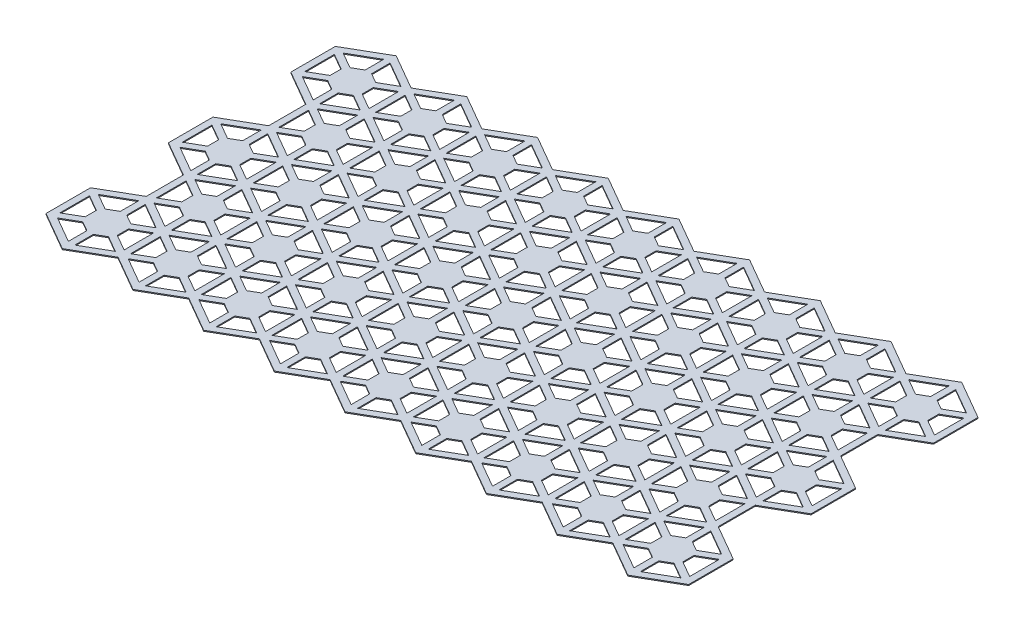
SolidWorks part; units mm, degrees
material "7075-T6 (SN)"
ref_plane "Front Plane" through (0, 0, 0) normal (0, 0, 1) x (1, 0, 0)
ref_plane "Top Plane" through (0, 0, 0) normal (0, 1, 0) x (1, 0, 0)
ref_plane "Right Plane" through (0, 0, 0) normal (1, 0, 0) x (0, 0, -1)
sketch "Sketch1" plane through (0, 0, 0) normal (0, 1, 0) x (1, 0, 0)
  line L0 (11, -7.5056) -> (1, -13.2791)
  line L2 (-100, 45.0231) -> (-100, 31.1718)
  line L7 (0, 11.547) -> (-10, 5.7735)
  line L8 (-10, 5.7735) -> (-10, -5.7735)
  line L9 (-10, -5.7735) -> (0, -11.547)
  line L10 (0, -11.547) -> (10, -5.7735)
  line L11 (10, -5.7735) -> (10, 5.7735)
  line L12 (10, 5.7735) -> (0, 11.547)
  line L13 (1, -13.2791) -> (1, -24.8261)
  line L14 (1, -24.8261) -> (11, -30.5996)
  line L15 (11, -30.5996) -> (21, -24.8261)
  line L16 (21, -24.8261) -> (21, -13.2791)
  line L17 (21, -13.2791) -> (11, -7.5056)
  line L18 (-11, -7.5056) -> (-21, -13.2791)
  line L19 (-21, -13.2791) -> (-21, -24.8261)
  line L20 (-21, -24.8261) -> (-11, -30.5996)
  line L21 (-11, -30.5996) -> (-1, -24.8261)
  line L22 (-1, -24.8261) -> (-1, -13.2791)
  line L23 (-1, -13.2791) -> (-11, -7.5056)
  line L24 (-22, 11.547) -> (-32, 5.7735)
  line L25 (-32, 5.7735) -> (-32, -5.7735)
  line L26 (-32, -5.7735) -> (-22, -11.547)
  line L27 (-22, -11.547) -> (-12, -5.7735)
  line L28 (-12, -5.7735) -> (-12, 5.7735)
  line L29 (-12, 5.7735) -> (-22, 11.547)
  line L30 (-33, -7.5056) -> (-43, -13.2791)
  line L31 (-43, -13.2791) -> (-43, -24.8261)
  line L32 (-43, -24.8261) -> (-33, -30.5996)
  line L33 (-33, -30.5996) -> (-23, -24.8261)
  line L34 (-23, -24.8261) -> (-23, -13.2791)
  line L35 (-23, -13.2791) -> (-33, -7.5056)
  line L36 (-44, 11.547) -> (-54, 5.7735)
  line L37 (-54, 5.7735) -> (-54, -5.7735)
  line L38 (-54, -5.7735) -> (-44, -11.547)
  line L39 (-44, -11.547) -> (-34, -5.7735)
  line L40 (-34, -5.7735) -> (-34, 5.7735)
  line L41 (-34, 5.7735) -> (-44, 11.547)
  line L42 (-55, -7.5056) -> (-65, -13.2791)
  line L43 (-65, -13.2791) -> (-65, -24.8261)
  line L44 (-65, -24.8261) -> (-55, -30.5996)
  line L45 (-55, -30.5996) -> (-45, -24.8261)
  line L46 (-45, -24.8261) -> (-45, -13.2791)
  line L47 (-45, -13.2791) -> (-55, -7.5056)
  line L48 (-66, 11.547) -> (-76, 5.7735)
  line L49 (-76, 5.7735) -> (-76, -5.7735)
  line L50 (-76, -5.7735) -> (-66, -11.547)
  line L51 (-66, -11.547) -> (-56, -5.7735)
  line L52 (-56, -5.7735) -> (-56, 5.7735)
  line L53 (-56, 5.7735) -> (-66, 11.547)
  line L54 (-77, -7.5056) -> (-87, -13.2791)
  line L55 (-87, -13.2791) -> (-87, -24.8261)
  line L56 (-87, -24.8261) -> (-77, -30.5996)
  line L57 (-77, -30.5996) -> (-67, -24.8261)
  line L58 (-67, -24.8261) -> (-67, -13.2791)
  line L59 (-67, -13.2791) -> (-77, -7.5056)
  line L60 (-88, 11.547) -> (-98, 5.7735)
  line L61 (-98, 5.7735) -> (-98, -5.7735)
  line L62 (-98, -5.7735) -> (-88, -11.547)
  line L63 (-88, -11.547) -> (-78, -5.7735)
  line L64 (-78, -5.7735) -> (-78, 5.7735)
  line L65 (-78, 5.7735) -> (-88, 11.547)
  line L69 (-100, -31.1769) -> (-89, -24.8261)
  line L70 (-89, -24.8261) -> (-89, -13.2791)
  line L71 (-89, -13.2791) -> (-100, -6.9282)
  line L76 (-100, -5.7735) -> (-100, 5.7735)
  line L78 (-11, -45.6056) -> (-21.9837, -51.947)
  line L83 (-0.0163, -51.947) -> (-11, -45.6056)
  line L84 (-22, -26.553) -> (-32, -32.3265)
  line L85 (-32, -32.3265) -> (-32, -43.8735)
  line L86 (-32, -43.8735) -> (-22, -49.647)
  line L87 (-22, -49.647) -> (-12, -43.8735)
  line L88 (-12, -43.8735) -> (-12, -32.3265)
  line L89 (-12, -32.3265) -> (-22, -26.553)
  line L90 (-33, -45.6056) -> (-43.9837, -51.947)
  line L95 (-22.0163, -51.947) -> (-33, -45.6056)
  line L96 (-44, -26.553) -> (-54, -32.3265)
  line L97 (-54, -32.3265) -> (-54, -43.8735)
  line L98 (-54, -43.8735) -> (-44, -49.647)
  line L99 (-44, -49.647) -> (-34, -43.8735)
  line L100 (-34, -43.8735) -> (-34, -32.3265)
  line L101 (-34, -32.3265) -> (-44, -26.553)
  line L102 (-55, -45.6056) -> (-65.9837, -51.947)
  line L107 (-44.0163, -51.947) -> (-55, -45.6056)
  line L108 (-66, -26.553) -> (-76, -32.3265)
  line L109 (-76, -32.3265) -> (-76, -43.8735)
  line L110 (-76, -43.8735) -> (-66, -49.647)
  line L111 (-66, -49.647) -> (-56, -43.8735)
  line L112 (-56, -43.8735) -> (-56, -32.3265)
  line L113 (-56, -32.3265) -> (-66, -26.553)
  line L114 (-77, -45.6056) -> (-87.9837, -51.947)
  line L119 (-66.0163, -51.947) -> (-77, -45.6056)
  line L120 (-88, -26.553) -> (-98, -32.3265)
  line L121 (-98, -32.3265) -> (-98, -43.8735)
  line L122 (-98, -43.8735) -> (-88, -49.647)
  line L123 (-88, -49.647) -> (-78, -43.8735)
  line L124 (-78, -43.8735) -> (-78, -32.3265)
  line L125 (-78, -32.3265) -> (-88, -26.553)
  line L131 (-89, -51.3791) -> (-100, -45.0282)
  line L136 (-100, -43.8735) -> (-100, -32.3265)
  line L138 (11, -45.6056) -> (0.0163, -51.947)
  line L143 (21.9837, -51.947) -> (11, -45.6056)
  line L144 (0, -26.553) -> (-10, -32.3265)
  line L145 (-10, -32.3265) -> (-10, -43.8735)
  line L146 (-10, -43.8735) -> (0, -49.647)
  line L147 (0, -49.647) -> (10, -43.8735)
  line L148 (10, -43.8735) -> (10, -32.3265)
  line L149 (10, -32.3265) -> (0, -26.553)
  line L150 (11, -7.5056) -> (-11, -7.5056) construction
  line L151 (22, 11.547) -> (12, 5.7735)
  line L152 (12, 5.7735) -> (12, -5.7735)
  line L153 (12, -5.7735) -> (22, -11.547)
  line L154 (22, -11.547) -> (32, -5.7735)
  line L155 (32, -5.7735) -> (32, 5.7735)
  line L156 (32, 5.7735) -> (22, 11.547)
  line L157 (33, -7.5056) -> (23, -13.2791)
  line L158 (23, -13.2791) -> (23, -24.8261)
  line L159 (23, -24.8261) -> (33, -30.5996)
  line L160 (33, -30.5996) -> (43, -24.8261)
  line L161 (43, -24.8261) -> (43, -13.2791)
  line L162 (43, -13.2791) -> (33, -7.5056)
  line L163 (44, 11.547) -> (34, 5.7735)
  line L164 (34, 5.7735) -> (34, -5.7735)
  line L165 (34, -5.7735) -> (44, -11.547)
  line L166 (44, -11.547) -> (54, -5.7735)
  line L167 (54, -5.7735) -> (54, 5.7735)
  line L168 (54, 5.7735) -> (44, 11.547)
  line L169 (55, -7.5056) -> (45, -13.2791)
  line L170 (45, -13.2791) -> (45, -24.8261)
  line L171 (45, -24.8261) -> (55, -30.5996)
  line L172 (55, -30.5996) -> (65, -24.8261)
  line L173 (65, -24.8261) -> (65, -13.2791)
  line L174 (65, -13.2791) -> (55, -7.5056)
  line L175 (66, 11.547) -> (56, 5.7735)
  line L176 (56, 5.7735) -> (56, -5.7735)
  line L177 (56, -5.7735) -> (66, -11.547)
  line L178 (66, -11.547) -> (76, -5.7735)
  line L179 (76, -5.7735) -> (76, 5.7735)
  line L180 (76, 5.7735) -> (66, 11.547)
  line L181 (77, -7.5056) -> (67, -13.2791)
  line L182 (67, -13.2791) -> (67, -24.8261)
  line L183 (67, -24.8261) -> (77, -30.5996)
  line L184 (77, -30.5996) -> (87, -24.8261)
  line L185 (87, -24.8261) -> (87, -13.2791)
  line L186 (87, -13.2791) -> (77, -7.5056)
  line L187 (88, 11.547) -> (78, 5.7735)
  line L188 (78, 5.7735) -> (78, -5.7735)
  line L189 (78, -5.7735) -> (88, -11.547)
  line L190 (88, -11.547) -> (98, -5.7735)
  line L191 (98, -5.7735) -> (98, 5.7735)
  line L192 (98, 5.7735) -> (88, 11.547)
  line L193 (95.3804, -9.5953) -> (89, -13.2791)
  line L194 (89, -13.2791) -> (89, -24.8261)
  line L195 (89, -24.8261) -> (95.3804, -28.5098)
  line L199 (22, 49.647) -> (12, 43.8735)
  line L200 (12, 43.8735) -> (12, 32.3265)
  line L201 (12, 32.3265) -> (22, 26.553)
  line L202 (22, 26.553) -> (32, 32.3265)
  line L203 (32, 32.3265) -> (32, 43.8735)
  line L204 (32, 43.8735) -> (22, 49.647)
  line L205 (33, 30.5944) -> (23, 24.8209)
  line L206 (23, 24.8209) -> (23, 13.2739)
  line L207 (23, 13.2739) -> (33, 7.5004)
  line L208 (33, 7.5004) -> (43, 13.2739)
  line L209 (43, 13.2739) -> (43, 24.8209)
  line L210 (43, 24.8209) -> (33, 30.5944)
  line L211 (44, 49.647) -> (34, 43.8735)
  line L212 (34, 43.8735) -> (34, 32.3265)
  line L213 (34, 32.3265) -> (44, 26.553)
  line L214 (44, 26.553) -> (54, 32.3265)
  line L215 (54, 32.3265) -> (54, 43.8735)
  line L216 (54, 43.8735) -> (44, 49.647)
  line L217 (55, 30.5944) -> (45, 24.8209)
  line L218 (45, 24.8209) -> (45, 13.2739)
  line L219 (45, 13.2739) -> (55, 7.5004)
  line L220 (55, 7.5004) -> (65, 13.2739)
  line L221 (65, 13.2739) -> (65, 24.8209)
  line L222 (65, 24.8209) -> (55, 30.5944)
  line L223 (66, 49.647) -> (56, 43.8735)
  line L224 (56, 43.8735) -> (56, 32.3265)
  line L225 (56, 32.3265) -> (66, 26.553)
  line L226 (66, 26.553) -> (76, 32.3265)
  line L227 (76, 32.3265) -> (76, 43.8735)
  line L228 (76, 43.8735) -> (66, 49.647)
  line L229 (77, 30.5944) -> (67, 24.8209)
  line L230 (67, 24.8209) -> (67, 13.2739)
  line L231 (67, 13.2739) -> (77, 7.5004)
  line L232 (77, 7.5004) -> (87, 13.2739)
  line L233 (87, 13.2739) -> (87, 24.8209)
  line L234 (87, 24.8209) -> (77, 30.5944)
  line L235 (88, 49.647) -> (78, 43.8735)
  line L236 (78, 43.8735) -> (78, 32.3265)
  line L237 (78, 32.3265) -> (88, 26.553)
  line L238 (88, 26.553) -> (98, 32.3265)
  line L239 (98, 32.3265) -> (98, 43.8735)
  line L240 (98, 43.8735) -> (88, 49.647)
  line L241 (100, 31.1718) -> (89, 24.8209)
  line L242 (89, 24.8209) -> (89, 13.2739)
  line L243 (89, 13.2739) -> (100, 6.9231)
  line L255 (22, 51.9513) -> (33, 45.6004)
  line L256 (33, 45.6004) -> (44, 51.9513)
  line L267 (44, 51.9513) -> (55, 45.6004)
  line L268 (55, 45.6004) -> (66, 51.9513)
  line L279 (66, 51.9513) -> (77, 45.6004)
  line L280 (77, 45.6004) -> (88, 51.9513)
  line L291 (88, 51.9513) -> (100, 45.0231)
  line L295 (0, 49.647) -> (-10, 43.8735)
  line L296 (-10, 43.8735) -> (-10, 32.3265)
  line L297 (-10, 32.3265) -> (0, 26.553)
  line L298 (0, 26.553) -> (10, 32.3265)
  line L299 (10, 32.3265) -> (10, 43.8735)
  line L300 (10, 43.8735) -> (0, 49.647)
  line L301 (11, 30.5944) -> (1, 24.8209)
  line L302 (1, 24.8209) -> (1, 13.2739)
  line L303 (1, 13.2739) -> (11, 7.5004)
  line L304 (11, 7.5004) -> (21, 13.2739)
  line L305 (21, 13.2739) -> (21, 24.8209)
  line L306 (21, 24.8209) -> (11, 30.5944)
  line L315 (0, 51.9513) -> (11, 45.6004)
  line L316 (11, 45.6004) -> (22, 51.9513)
  line L319 (0, 11.547) -> (22, 11.547) construction
  line L320 (-11, 30.5944) -> (-21, 24.8209)
  line L321 (-21, 24.8209) -> (-21, 13.2739)
  line L322 (-21, 13.2739) -> (-11, 7.5004)
  line L323 (-11, 7.5004) -> (-1, 13.2739)
  line L324 (-1, 13.2739) -> (-1, 24.8209)
  line L325 (-1, 24.8209) -> (-11, 30.5944)
  line L326 (-22, 11.547) -> (-32, 5.7735)
  line L327 (-32, 5.7735) -> (-32, -5.7735)
  line L328 (-32, -5.7735) -> (-22, -11.547)
  line L329 (-22, -11.547) -> (-12, -5.7735)
  line L330 (-12, -5.7735) -> (-12, 5.7735)
  line L331 (-12, 5.7735) -> (-22, 11.547)
  line L332 (-33, 30.5944) -> (-43, 24.8209)
  line L333 (-43, 24.8209) -> (-43, 13.2739)
  line L334 (-43, 13.2739) -> (-33, 7.5004)
  line L335 (-33, 7.5004) -> (-23, 13.2739)
  line L336 (-23, 13.2739) -> (-23, 24.8209)
  line L337 (-23, 24.8209) -> (-33, 30.5944)
  line L338 (-44, 11.547) -> (-54, 5.7735)
  line L339 (-54, 5.7735) -> (-54, -5.7735)
  line L340 (-54, -5.7735) -> (-44, -11.547)
  line L341 (-44, -11.547) -> (-34, -5.7735)
  line L342 (-34, -5.7735) -> (-34, 5.7735)
  line L343 (-34, 5.7735) -> (-44, 11.547)
  line L344 (-55, 30.5944) -> (-65, 24.8209)
  line L345 (-65, 24.8209) -> (-65, 13.2739)
  line L346 (-65, 13.2739) -> (-55, 7.5004)
  line L347 (-55, 7.5004) -> (-45, 13.2739)
  line L348 (-45, 13.2739) -> (-45, 24.8209)
  line L349 (-45, 24.8209) -> (-55, 30.5944)
  line L350 (-66, 11.547) -> (-76, 5.7735)
  line L351 (-76, 5.7735) -> (-76, -5.7735)
  line L352 (-76, -5.7735) -> (-66, -11.547)
  line L353 (-66, -11.547) -> (-56, -5.7735)
  line L354 (-56, -5.7735) -> (-56, 5.7735)
  line L355 (-56, 5.7735) -> (-66, 11.547)
  line L356 (-77, 30.5944) -> (-87, 24.8209)
  line L357 (-87, 24.8209) -> (-87, 13.2739)
  line L358 (-87, 13.2739) -> (-77, 7.5004)
  line L359 (-77, 7.5004) -> (-67, 13.2739)
  line L360 (-67, 13.2739) -> (-67, 24.8209)
  line L361 (-67, 24.8209) -> (-77, 30.5944)
  line L362 (-88, 11.547) -> (-98, 5.7735)
  line L363 (-98, 5.7735) -> (-98, -5.7735)
  line L364 (-98, -5.7735) -> (-88, -11.547)
  line L365 (-88, -11.547) -> (-78, -5.7735)
  line L366 (-78, -5.7735) -> (-78, 5.7735)
  line L367 (-78, 5.7735) -> (-88, 11.547)
  line L371 (-100, 6.9231) -> (-89, 13.2739)
  line L372 (-89, 13.2739) -> (-89, 24.8209)
  line L373 (-89, 24.8209) -> (-100, 31.1718)
  line L378 (-100, -5.7735) -> (-100, 5.7735)
  line L382 (-22, 51.9513) -> (-11, 45.6004)
  line L383 (-11, 45.6004) -> (0, 51.9513)
  line L386 (-22, 49.647) -> (-32, 43.8735)
  line L387 (-32, 43.8735) -> (-32, 32.3265)
  line L388 (-32, 32.3265) -> (-22, 26.553)
  line L389 (-22, 26.553) -> (-12, 32.3265)
  line L390 (-12, 32.3265) -> (-12, 43.8735)
  line L391 (-12, 43.8735) -> (-22, 49.647)
  line L394 (-44, 51.9513) -> (-33, 45.6004)
  line L395 (-33, 45.6004) -> (-22, 51.9513)
  line L398 (-44, 49.647) -> (-54, 43.8735)
  line L399 (-54, 43.8735) -> (-54, 32.3265)
  line L400 (-54, 32.3265) -> (-44, 26.553)
  line L401 (-44, 26.553) -> (-34, 32.3265)
  line L402 (-34, 32.3265) -> (-34, 43.8735)
  line L403 (-34, 43.8735) -> (-44, 49.647)
  line L406 (-66, 51.9513) -> (-55, 45.6004)
  line L407 (-55, 45.6004) -> (-44, 51.9513)
  line L410 (-66, 49.647) -> (-76, 43.8735)
  line L411 (-76, 43.8735) -> (-76, 32.3265)
  line L412 (-76, 32.3265) -> (-66, 26.553)
  line L413 (-66, 26.553) -> (-56, 32.3265)
  line L414 (-56, 32.3265) -> (-56, 43.8735)
  line L415 (-56, 43.8735) -> (-66, 49.647)
  line L418 (-87, 51.3739) -> (-77, 45.6004)
  line L419 (-77, 45.6004) -> (-66, 51.9513)
  line L422 (-88, 49.647) -> (-98, 43.8735)
  line L423 (-98, 43.8735) -> (-98, 32.3265)
  line L424 (-98, 32.3265) -> (-88, 26.553)
  line L425 (-88, 26.553) -> (-78, 32.3265)
  line L426 (-78, 32.3265) -> (-78, 43.8735)
  line L427 (-78, 43.8735) -> (-88, 49.647)
  line L431 (-100, 45.0231) -> (-89, 51.3739)
  line L438 (-100, 32.3265) -> (-100, 43.8735)
  line L442 (1, 51.3739) -> (11, 45.6004)
  line L443 (11, 45.6004) -> (21, 51.3739)
  line L446 (0, 49.647) -> (-10, 43.8735)
  line L447 (-10, 43.8735) -> (-10, 32.3265)
  line L448 (-10, 32.3265) -> (0, 26.553)
  line L449 (0, 26.553) -> (10, 32.3265)
  line L450 (10, 32.3265) -> (10, 43.8735)
  line L451 (10, 43.8735) -> (0, 49.647)
  line L452 (11, 30.5944) -> (-11, 30.5944) construction
  line L453 (22, -26.553) -> (12, -32.3265)
  line L454 (12, -32.3265) -> (12, -43.8735)
  line L455 (12, -43.8735) -> (22, -49.647)
  line L456 (22, -49.647) -> (32, -43.8735)
  line L457 (32, -43.8735) -> (32, -32.3265)
  line L458 (32, -32.3265) -> (22, -26.553)
  line L459 (33, -7.5056) -> (23, -13.2791)
  line L460 (23, -13.2791) -> (23, -24.8261)
  line L461 (23, -24.8261) -> (33, -30.5996)
  line L462 (33, -30.5996) -> (43, -24.8261)
  line L463 (43, -24.8261) -> (43, -13.2791)
  line L464 (43, -13.2791) -> (33, -7.5056)
  line L465 (44, -26.553) -> (34, -32.3265)
  line L466 (34, -32.3265) -> (34, -43.8735)
  line L467 (34, -43.8735) -> (44, -49.647)
  line L468 (44, -49.647) -> (54, -43.8735)
  line L469 (54, -43.8735) -> (54, -32.3265)
  line L470 (54, -32.3265) -> (44, -26.553)
  line L471 (55, -7.5056) -> (45, -13.2791)
  line L472 (45, -13.2791) -> (45, -24.8261)
  line L473 (45, -24.8261) -> (55, -30.5996)
  line L474 (55, -30.5996) -> (65, -24.8261)
  line L475 (65, -24.8261) -> (65, -13.2791)
  line L476 (65, -13.2791) -> (55, -7.5056)
  line L477 (66, -26.553) -> (56, -32.3265)
  line L478 (56, -32.3265) -> (56, -43.8735)
  line L479 (56, -43.8735) -> (66, -49.647)
  line L480 (66, -49.647) -> (76, -43.8735)
  line L481 (76, -43.8735) -> (76, -32.3265)
  line L482 (76, -32.3265) -> (66, -26.553)
  line L483 (77, -7.5056) -> (67, -13.2791)
  line L484 (67, -13.2791) -> (67, -24.8261)
  line L485 (67, -24.8261) -> (77, -30.5996)
  line L486 (77, -30.5996) -> (87, -24.8261)
  line L487 (87, -24.8261) -> (87, -13.2791)
  line L488 (87, -13.2791) -> (77, -7.5056)
  line L489 (88, -26.553) -> (78, -32.3265)
  line L490 (78, -32.3265) -> (78, -43.8735)
  line L491 (78, -43.8735) -> (88, -49.647)
  line L492 (88, -49.647) -> (98, -43.8735)
  line L493 (98, -43.8735) -> (98, -32.3265)
  line L494 (98, -32.3265) -> (88, -26.553)
  line L495 (100, -6.9282) -> (89, -13.2791)
  line L496 (89, -13.2791) -> (89, -24.8261)
  line L497 (89, -24.8261) -> (100, -31.1769)
  line L507 (33, -45.6056) -> (22.0163, -51.947)
  line L512 (43.9837, -51.947) -> (33, -45.6056)
  line L519 (55, -45.6056) -> (44.0163, -51.947)
  line L524 (65.9837, -51.947) -> (55, -45.6056)
  line L531 (77, -45.6056) -> (66.0163, -51.947)
  line L536 (87.9837, -51.947) -> (77, -45.6056)
  line L543 (100, -45.0282) -> (89, -51.3791)
  line L555 (11, -45.6056) -> (1, -51.3791)
  line L560 (21, -51.3791) -> (11, -45.6056)
  line L561 (0, -26.553) -> (22, -26.553) construction
  line L562 (-21, -51.3791) -> (-21, -62.9261) [skipped]
  line L563 (-21, -62.9261) -> (-11, -68.6996) [skipped]
  line L564 (-11, -68.6996) -> (-1, -62.9261) [skipped]
  line L565 (-1, -62.9261) -> (-1, -51.3791) [skipped]
  line L566 (-43, -51.3791) -> (-43, -62.9261) [skipped]
  line L567 (-43, -62.9261) -> (-33, -68.6996) [skipped]
  line L568 (-33, -68.6996) -> (-23, -62.9261) [skipped]
  line L569 (-23, -62.9261) -> (-23, -51.3791) [skipped]
  line L570 (-65, -51.3791) -> (-65, -62.9261) [skipped]
  line L571 (-65, -62.9261) -> (-55, -68.6996) [skipped]
  line L572 (-55, -68.6996) -> (-45, -62.9261) [skipped]
  line L573 (-45, -62.9261) -> (-45, -51.3791) [skipped]
  line L574 (-87, -51.3791) -> (-87, -62.9261) [skipped]
  line L575 (-87, -62.9261) -> (-77, -68.6996) [skipped]
  line L576 (-77, -68.6996) -> (-67, -62.9261) [skipped]
  line L577 (-67, -62.9261) -> (-67, -51.3791) [skipped]
  line L578 (-109, -51.3791) -> (-109, -62.9261) [skipped]
  line L579 (-109, -62.9261) -> (-99, -68.6996) [skipped]
  line L580 (-99, -68.6996) -> (-89, -62.9261) [skipped]
  line L581 (-89, -62.9261) -> (-89, -51.3791) [skipped]
  line L582 (1, -51.3791) -> (1, -62.9261) [skipped]
  line L583 (1, -62.9261) -> (11, -68.6996) [skipped]
  line L584 (11, -68.6996) -> (21, -62.9261) [skipped]
  line L585 (21, -62.9261) -> (21, -51.3791) [skipped]
  line L586 (22, -64.653) -> (12, -70.4265) [skipped]
  line L587 (12, -70.4265) -> (12, -81.9735) [skipped]
  line L588 (12, -81.9735) -> (22, -87.747) [skipped]
  line L589 (22, -87.747) -> (32, -81.9735) [skipped]
  line L590 (32, -81.9735) -> (32, -70.4265) [skipped]
  line L591 (32, -70.4265) -> (22, -64.653) [skipped]
  line L592 (23, -51.3791) -> (23, -62.9261) [skipped]
  line L593 (23, -62.9261) -> (33, -68.6996) [skipped]
  line L594 (33, -68.6996) -> (43, -62.9261) [skipped]
  line L595 (43, -62.9261) -> (43, -51.3791) [skipped]
  line L596 (44, -64.653) -> (34, -70.4265) [skipped]
  line L597 (34, -70.4265) -> (34, -81.9735) [skipped]
  line L598 (34, -81.9735) -> (44, -87.747) [skipped]
  line L599 (44, -87.747) -> (54, -81.9735) [skipped]
  line L600 (54, -81.9735) -> (54, -70.4265) [skipped]
  line L601 (54, -70.4265) -> (44, -64.653) [skipped]
  line L602 (45, -51.3791) -> (45, -62.9261) [skipped]
  line L603 (45, -62.9261) -> (55, -68.6996) [skipped]
  line L604 (55, -68.6996) -> (65, -62.9261) [skipped]
  line L605 (65, -62.9261) -> (65, -51.3791) [skipped]
  line L606 (66, -64.653) -> (56, -70.4265) [skipped]
  line L607 (56, -70.4265) -> (56, -81.9735) [skipped]
  line L608 (56, -81.9735) -> (66, -87.747) [skipped]
  line L609 (66, -87.747) -> (76, -81.9735) [skipped]
  line L610 (76, -81.9735) -> (76, -70.4265) [skipped]
  line L611 (76, -70.4265) -> (66, -64.653) [skipped]
  line L612 (67, -51.3791) -> (67, -62.9261) [skipped]
  line L613 (67, -62.9261) -> (77, -68.6996) [skipped]
  line L614 (77, -68.6996) -> (87, -62.9261) [skipped]
  line L615 (87, -62.9261) -> (87, -51.3791) [skipped]
  line L616 (88, -64.653) -> (78, -70.4265) [skipped]
  line L617 (78, -70.4265) -> (78, -81.9735) [skipped]
  line L618 (78, -81.9735) -> (88, -87.747) [skipped]
  line L619 (88, -87.747) -> (98, -81.9735) [skipped]
  line L620 (98, -81.9735) -> (98, -70.4265) [skipped]
  line L621 (98, -70.4265) -> (88, -64.653) [skipped]
  line L622 (89, -51.3791) -> (89, -62.9261) [skipped]
  line L623 (89, -62.9261) -> (99, -68.6996) [skipped]
  line L624 (99, -68.6996) -> (109, -62.9261) [skipped]
  line L625 (109, -62.9261) -> (109, -51.3791) [skipped]
  line L626 (0, -64.653) -> (-10, -70.4265) [skipped]
  line L627 (-10, -70.4265) -> (-10, -81.9735) [skipped]
  line L628 (-10, -81.9735) -> (0, -87.747) [skipped]
  line L629 (0, -87.747) -> (10, -81.9735) [skipped]
  line L630 (10, -81.9735) -> (10, -70.4265) [skipped]
  line L631 (10, -70.4265) -> (0, -64.653) [skipped]
  line L632 (1, -51.3791) -> (1, -62.9261) [skipped]
  line L633 (1, -62.9261) -> (11, -68.6996) [skipped]
  line L634 (11, -68.6996) -> (21, -62.9261) [skipped]
  line L635 (21, -62.9261) -> (21, -51.3791) [skipped]
  line L636 (22, 87.747) -> (12, 81.9735) [skipped]
  line L637 (12, 81.9735) -> (12, 70.4265) [skipped]
  line L638 (12, 70.4265) -> (22, 64.653) [skipped]
  line L639 (22, 64.653) -> (32, 70.4265) [skipped]
  line L640 (32, 70.4265) -> (32, 81.9735) [skipped]
  line L641 (32, 81.9735) -> (22, 87.747) [skipped]
  line L642 (33, 68.6944) -> (23, 62.9209) [skipped]
  line L643 (23, 62.9209) -> (23, 51.3739) [skipped]
  line L644 (43, 51.3739) -> (43, 62.9209) [skipped]
  line L645 (43, 62.9209) -> (33, 68.6944) [skipped]
  line L646 (44, 87.747) -> (34, 81.9735) [skipped]
  line L647 (34, 81.9735) -> (34, 70.4265) [skipped]
  line L648 (34, 70.4265) -> (44, 64.653) [skipped]
  line L649 (44, 64.653) -> (54, 70.4265) [skipped]
  line L650 (54, 70.4265) -> (54, 81.9735) [skipped]
  line L651 (54, 81.9735) -> (44, 87.747) [skipped]
  line L652 (55, 68.6944) -> (45, 62.9209) [skipped]
  line L653 (45, 62.9209) -> (45, 51.3739) [skipped]
  line L654 (65, 51.3739) -> (65, 62.9209) [skipped]
  line L655 (65, 62.9209) -> (55, 68.6944) [skipped]
  line L656 (66, 87.747) -> (56, 81.9735) [skipped]
  line L657 (56, 81.9735) -> (56, 70.4265) [skipped]
  line L658 (56, 70.4265) -> (66, 64.653) [skipped]
  line L659 (66, 64.653) -> (76, 70.4265) [skipped]
  line L660 (76, 70.4265) -> (76, 81.9735) [skipped]
  line L661 (76, 81.9735) -> (66, 87.747) [skipped]
  line L662 (77, 68.6944) -> (67, 62.9209) [skipped]
  line L663 (67, 62.9209) -> (67, 51.3739) [skipped]
  line L664 (87, 51.3739) -> (87, 62.9209) [skipped]
  line L665 (87, 62.9209) -> (77, 68.6944) [skipped]
  line L666 (88, 87.747) -> (78, 81.9735) [skipped]
  line L667 (78, 81.9735) -> (78, 70.4265) [skipped]
  line L668 (78, 70.4265) -> (88, 64.653) [skipped]
  line L669 (88, 64.653) -> (98, 70.4265) [skipped]
  line L670 (98, 70.4265) -> (98, 81.9735) [skipped]
  line L671 (98, 81.9735) -> (88, 87.747) [skipped]
  line L672 (99, 68.6944) -> (89, 62.9209) [skipped]
  line L673 (89, 62.9209) -> (89, 51.3739) [skipped]
  line L674 (109, 51.3739) -> (109, 62.9209) [skipped]
  line L675 (109, 62.9209) -> (99, 68.6944) [skipped]
  line L676 (0, 87.747) -> (-10, 81.9735) [skipped]
  line L677 (-10, 81.9735) -> (-10, 70.4265) [skipped]
  line L678 (-10, 70.4265) -> (0, 64.653) [skipped]
  line L679 (0, 64.653) -> (10, 70.4265) [skipped]
  line L680 (10, 70.4265) -> (10, 81.9735) [skipped]
  line L681 (10, 81.9735) -> (0, 87.747) [skipped]
  line L682 (11, 68.6944) -> (1, 62.9209) [skipped]
  line L683 (1, 62.9209) -> (1, 51.3739) [skipped]
  line L684 (21, 51.3739) -> (21, 62.9209) [skipped]
  line L685 (21, 62.9209) -> (11, 68.6944) [skipped]
  line L686 (-11, 68.6944) -> (-21, 62.9209) [skipped]
  line L687 (-21, 62.9209) -> (-21, 51.3739) [skipped]
  line L688 (-1, 51.3739) -> (-1, 62.9209) [skipped]
  line L689 (-1, 62.9209) -> (-11, 68.6944) [skipped]
  line L690 (-33, 68.6944) -> (-43, 62.9209) [skipped]
  line L691 (-43, 62.9209) -> (-43, 51.3739) [skipped]
  line L692 (-23, 51.3739) -> (-23, 62.9209) [skipped]
  line L693 (-23, 62.9209) -> (-33, 68.6944) [skipped]
  line L694 (-55, 68.6944) -> (-65, 62.9209) [skipped]
  line L695 (-65, 62.9209) -> (-65, 51.3739) [skipped]
  line L696 (-45, 51.3739) -> (-45, 62.9209) [skipped]
  line L697 (-45, 62.9209) -> (-55, 68.6944) [skipped]
  line L698 (-77, 68.6944) -> (-87, 62.9209) [skipped]
  line L699 (-87, 62.9209) -> (-87, 51.3739) [skipped]
  line L700 (-67, 51.3739) -> (-67, 62.9209) [skipped]
  line L701 (-67, 62.9209) -> (-77, 68.6944) [skipped]
  line L702 (-99, 68.6944) -> (-109, 62.9209) [skipped]
  line L703 (-109, 62.9209) -> (-109, 51.3739) [skipped]
  line L704 (-89, 51.3739) -> (-89, 62.9209) [skipped]
  line L705 (-89, 62.9209) -> (-99, 68.6944) [skipped]
  line L706 (11, 68.6944) -> (1, 62.9209) [skipped]
  line L707 (1, 62.9209) -> (1, 51.3739) [skipped]
  line L708 (21, 51.3739) -> (21, 62.9209) [skipped]
  line L709 (21, 62.9209) -> (11, 68.6944) [skipped]
  line L710 (99, -30.5996) -> (109, -24.8261) [skipped]
  line L711 (109, -24.8261) -> (109, -13.2791) [skipped]
  line L712 (109, -13.2791) -> (99, -7.5056) [skipped]
  line L713 (99, 7.5004) -> (109, 13.2739) [skipped]
  line L714 (109, 13.2739) -> (109, 24.8209) [skipped]
  line L715 (109, 24.8209) -> (99, 30.5944) [skipped]
  line L716 (99, 45.6004) -> (109, 51.3739) [skipped]
  line L717 (99, -30.5996) -> (109, -24.8261) [skipped]
  line L718 (109, -24.8261) -> (109, -13.2791) [skipped]
  line L719 (109, -13.2791) -> (99, -7.5056) [skipped]
  line L720 (109, -51.3791) -> (99, -45.6056) [skipped]
  line L721 (-109, -13.2791) -> (-109, -24.8261) [skipped]
  line L722 (-110, 11.547) -> (-120, 5.7735) [skipped]
  line L723 (-120, 5.7735) -> (-120, -5.7735) [skipped]
  line L724 (-120, -5.7735) -> (-110, -11.547) [skipped]
  line L725 (-110, -26.553) -> (-120, -32.3265) [skipped]
  line L726 (-120, -32.3265) -> (-120, -43.8735) [skipped]
  line L727 (-120, -43.8735) -> (-110, -49.647) [skipped]
  line L728 (-109, 24.8209) -> (-109, 13.2739) [skipped]
  line L729 (-110, 11.547) -> (-120, 5.7735) [skipped]
  line L730 (-120, 5.7735) -> (-120, -5.7735) [skipped]
  line L731 (-120, -5.7735) -> (-110, -11.547) [skipped]
  line L732 (-110, 49.647) -> (-120, 43.8735) [skipped]
  line L733 (-120, 43.8735) -> (-120, 32.3265) [skipped]
  line L734 (-120, 32.3265) -> (-110, 26.553) [skipped]
  line L735 (-99, -7.5056) -> (-109, -13.2791) [skipped]
  line L736 (-109, -24.8261) -> (-99, -30.5996) [skipped]
  line L737 (-110, -11.547) -> (-100, -5.7735) [skipped]
  line L738 (-100, 5.7735) -> (-110, 11.547) [skipped]
  line L739 (-99, -45.6056) -> (-109, -51.3791) [skipped]
  line L740 (-110, -49.647) -> (-100, -43.8735) [skipped]
  line L741 (-100, -32.3265) -> (-110, -26.553) [skipped]
  line L742 (-99, 30.5944) -> (-109, 24.8209) [skipped]
  line L743 (-109, 13.2739) -> (-99, 7.5004) [skipped]
  line L744 (-110, -11.547) -> (-100, -5.7735) [skipped]
  line L745 (-100, 5.7735) -> (-110, 11.547) [skipped]
  line L746 (-109, 51.3739) -> (-99, 45.6004) [skipped]
  line L747 (-110, 26.553) -> (-100, 32.3265) [skipped]
  line L748 (-100, 43.8735) -> (-110, 49.647) [skipped]
  line L749 (-100, -31.1769) -> (-100, -45.0282)
  line L751 (-100, 6.9231) -> (-100, -6.9282)
  line L752 (100, 45.0231) -> (100, 31.1718)
  line L753 (-87, 51.3739) -> (-88, 51.9513)
  line L754 (100, 6.9231) -> (100, -6.9282)
  line L755 (-89, 51.3739) -> (-88, 51.9513)
  line L756 (100, -31.1769) -> (100, -45.0282)
  line L757 (-88, -51.947) -> (-87.9837, -51.947)
  line L758 (-89, -51.3791) -> (-88, -51.947)
  line L759 (89, -51.3791) -> (88, -51.947)
  line L760 (87.9837, -51.947) -> (88, -51.947)
  line L761 (65.9837, -51.947) -> (66.0163, -51.947)
  line L762 (43.9837, -51.947) -> (44.0163, -51.947)
  line L763 (21.9837, -51.947) -> (22.0163, -51.947)
  line L764 (-0.0163, -51.947) -> (0.0163, -51.947)
  line L765 (-22.0163, -51.947) -> (-21.9837, -51.947)
  line L766 (-44.0163, -51.947) -> (-43.9837, -51.947)
  line L767 (-66.0163, -51.947) -> (-65.9837, -51.947)
  circle A0 centre (0, 0) radius 10 construction
  point P0 (0, 0)
  dimension "D2" = 2
  dimension "D3" = 20
  dimension "D4" = 20
  dimension "D5" = 23.094
  dimension "D6" = 2
  dimension "D7" = 1
  dimension "D8" = 36.3731
  dimension "D10" = 2.3
  dimension "D13" = 22
  dimension "D16" = 22
  dimension "D18" = 22
  dimension "D20" = 5
  dimension "D21" = 103.8983
  dimension "D22" = 200
  dimension "D11" = 6
  dimension "D9" = 2
  dimension "D14" = 5
  dimension "D12" = 3
  dimension "D19" = 6
  dimension "D15" = 2
  dimension "D17" = 2
extrude "Boss-Extrude1" add sketch "Sketch1" along normal blind 0.3 contours L119 L767 L102 L107 L766 L90 L95 L765 L78 L83 L764 L138 L143 L763 L507 L512 L762 L519 L524 L761 L531 L536 L760 L759 L543 L756 L497 L195 L194 L193 L495 L754 L243 L242 L241 L752 L291 L280 L279 L268 L267 L256 L255 L316 L315 L383 L382 region at (-98.3731, 0, -43.3599)
sketch "Sketch2" plane through (0, 0.3, 0) normal (0, 1, 0) x (1, 0, 0)
  line L1 (-1, 5.1962) -> (-4, 3.4641)
  line L2 (-5, 1.7321) -> (-5, -1.7321)
  line L3 (-4, -3.4641) -> (-1, -5.1962)
  line L4 (1, -5.1962) -> (4, -3.4641)
  line L5 (5, -1.7321) -> (5, 1.7321)
  line L6 (4, 3.4641) -> (1, 5.1962)
  line L12 (-1, -10.9697) -> (-1, -5.1962)
  line L13 (0, 4.6188) -> (-4, 2.3094)
  line L14 (-4, 2.3094) -> (-4, -2.3094)
  line L15 (-4, -2.3094) -> (0, -4.6188)
  line L16 (0, -4.6188) -> (4, -2.3094)
  line L17 (4, -2.3094) -> (4, 2.3094)
  line L18 (4, 2.3094) -> (0, 4.6188)
  line L22 (11, -14.4338) -> (7, -16.7432)
  line L23 (7, -16.7432) -> (7, -21.362)
  line L24 (7, -21.362) -> (11, -23.6714)
  line L25 (11, -23.6714) -> (15, -21.362)
  line L26 (15, -21.362) -> (15, -16.7432)
  line L27 (15, -16.7432) -> (11, -14.4338)
  line L28 (1, -10.9697) -> (1, -5.1962)
  line L29 (5, -1.7321) -> (10, -4.6188)
  line L30 (1, 5.1962) -> (1, 10.9697)
  line L31 (0, 11.547) -> (-1, 10.9697)
  line L32 (0, 11.547) -> (-10, 5.7735) construction
  line L34 (1, 10.9697) -> (0, 11.547)
  line L35 (0, -11.547) -> (-1, -10.9697)
  line L36 (-10, -5.7735) -> (0, -11.547) construction
  line L38 (0, -11.547) -> (10, -5.7735) construction
  line L39 (1, -10.9697) -> (0, -11.547)
  line L40 (4, -3.4641) -> (9, -6.3509)
  line L41 (-1, 5.1962) -> (-1, 10.9697)
  line L42 (10, -5.7735) -> (10, -4.6188)
  line L43 (9, -6.3509) -> (10, -5.7735)
  line L44 (-10, 4.6188) -> (-5, 1.7321)
  line L45 (-9, 6.3509) -> (-4, 3.4641)
  line L46 (-10, 5.7735) -> (-9, 6.3509)
  line L47 (-10, 4.6188) -> (-10, 5.7735)
  line L48 (-4, -3.4641) -> (-9, -6.3509)
  line L50 (-10, -5.7735) -> (-9, -6.3509)
  line L51 (-10, -4.6188) -> (-10, -5.7735)
  line L52 (9, 6.3509) -> (4, 3.4641)
  line L53 (10, 4.6188) -> (5, 1.7321)
  line L54 (10, 5.7735) -> (10, 4.6188)
  line L55 (9, 6.3509) -> (10, 5.7735)
  line L56 (-5, -1.7321) -> (-10, -4.6188)
  line L57 (-4, -1.1547) -> (-4.7426, -1.5835) [skipped]
  line L61 (-10, 5.7735) -> (10, -5.7735) construction
  line L62 (10, 5.7735) -> (-10, -5.7735) construction
  line L64 (12, -4.6188) -> (12, -5.7735)
  line L68 (12, -5.7735) -> (13, -6.3509)
  line L70 (18, -3.4641) -> (13, -6.3509)
  line L72 (10, -13.8564) -> (7, -15.5885)
  line L73 (6, -17.3205) -> (6, -20.7846)
  line L74 (7, -22.5167) -> (10, -24.2487)
  line L75 (12, -24.2487) -> (15, -22.5167)
  line L76 (16, -20.7846) -> (16, -17.3205)
  line L77 (15, -15.5885) -> (12, -13.8564)
  line L78 (10, -30.0222) -> (10, -24.2487)
  line L79 (12, -30.0222) -> (12, -24.2487)
  line L80 (16, -20.7846) -> (21, -23.6714)
  line L81 (12, -13.8564) -> (12, -8.0829)
  line L82 (11, -7.5056) -> (10, -8.0829)
  line L83 (12, -8.0829) -> (11, -7.5056)
  line L84 (11, -30.5996) -> (10, -30.0222)
  line L85 (12, -30.0222) -> (11, -30.5996)
  line L86 (15, -22.5167) -> (20, -25.4034)
  line L87 (10, -13.8564) -> (10, -8.0829)
  line L88 (21, -24.8261) -> (21, -23.6714)
  line L89 (20, -25.4034) -> (21, -24.8261)
  line L90 (1, -14.4338) -> (6, -17.3205)
  line L91 (2, -12.7017) -> (7, -15.5885)
  line L92 (1, -13.2791) -> (2, -12.7017)
  line L93 (1, -14.4338) -> (1, -13.2791)
  line L94 (7, -22.5167) -> (2, -25.4034)
  line L95 (1, -24.8261) -> (2, -25.4034)
  line L96 (1, -23.6714) -> (1, -24.8261)
  line L97 (20, -12.7017) -> (15, -15.5885)
  line L98 (21, -14.4338) -> (16, -17.3205)
  line L99 (21, -13.2791) -> (21, -14.4338)
  line L100 (20, -12.7017) -> (21, -13.2791)
  line L101 (6, -20.7846) -> (1, -23.6714)
  line L102 (1, -13.2791) -> (21, -24.8261) construction
  line L103 (21, -13.2791) -> (1, -24.8261) construction
  line L104 (18, -3.4641) -> (21, -5.1962)
  line L105 (21, -10.9697) -> (21, -5.1962)
  line L106 (22, -11.547) -> (21, -10.9697)
  line L107 (23, -10.9697) -> (22, -11.547)
  line L108 (23, -10.9697) -> (23, -5.1962)
  line L109 (23, -5.1962) -> (26, -3.4641)
  line L110 (26, -3.4641) -> (31, -6.3509)
  line L111 (31, -6.3509) -> (32, -5.7735)
  line L112 (32, -5.7735) -> (32, -4.6188)
  line L113 (27, -1.7321) -> (32, -4.6188)
  line L114 (27, -1.7321) -> (27, 1.7321)
  line L115 (32, 4.6188) -> (27, 1.7321)
  line L116 (32, 5.7735) -> (32, 4.6188)
  line L117 (31, 6.3509) -> (32, 5.7735)
  line L118 (31, 6.3509) -> (26, 3.4641)
  line L119 (26, 3.4641) -> (23, 5.1962)
  line L120 (23, 5.1962) -> (23, 10.9697)
  line L121 (23, 10.9697) -> (22, 11.547)
  line L122 (22, 11.547) -> (21, 10.9697)
  line L123 (21, 5.1962) -> (21, 10.9697)
  line L124 (21, 5.1962) -> (18, 3.4641)
  line L125 (13, 6.3509) -> (18, 3.4641)
  line L126 (12, 5.7735) -> (13, 6.3509)
  line L127 (12, 4.6188) -> (12, 5.7735)
  line L128 (12, 4.6188) -> (17, 1.7321)
  line L129 (17, 1.7321) -> (17, -1.7321)
  line L130 (17, -1.7321) -> (12, -4.6188)
  line L131 (32, -13.8564) -> (29, -15.5885)
  line L132 (24, -12.7017) -> (29, -15.5885)
  line L133 (23, -13.2791) -> (24, -12.7017)
  line L134 (23, -14.4338) -> (23, -13.2791)
  line L135 (23, -14.4338) -> (28, -17.3205)
  line L136 (28, -17.3205) -> (28, -20.7846)
  line L137 (28, -20.7846) -> (23, -23.6714)
  line L138 (23, -23.6714) -> (23, -24.8261)
  line L139 (23, -24.8261) -> (24, -25.4034)
  line L140 (29, -22.5167) -> (24, -25.4034)
  line L141 (29, -22.5167) -> (32, -24.2487)
  line L142 (32, -30.0222) -> (32, -24.2487)
  line L143 (33, -30.5996) -> (32, -30.0222)
  line L144 (34, -30.0222) -> (33, -30.5996)
  line L145 (34, -30.0222) -> (34, -24.2487)
  line L146 (34, -24.2487) -> (37, -22.5167)
  line L147 (37, -22.5167) -> (42, -25.4034)
  line L148 (42, -25.4034) -> (43, -24.8261)
  line L149 (43, -24.8261) -> (43, -23.6714)
  line L150 (38, -20.7846) -> (43, -23.6714)
  line L151 (38, -20.7846) -> (38, -17.3205)
  line L152 (43, -14.4338) -> (38, -17.3205)
  line L153 (43, -13.2791) -> (43, -14.4338)
  line L154 (42, -12.7017) -> (43, -13.2791)
  line L155 (42, -12.7017) -> (37, -15.5885)
  line L156 (37, -15.5885) -> (34, -13.8564)
  line L157 (34, -13.8564) -> (34, -8.0829)
  line L158 (34, -8.0829) -> (33, -7.5056)
  line L159 (33, -7.5056) -> (32, -8.0829)
  line L160 (32, -13.8564) -> (32, -8.0829)
  line L161 (34, -4.6188) -> (34, -5.7735)
  line L162 (34, -5.7735) -> (35, -6.3509)
  line L163 (40, -3.4641) -> (35, -6.3509)
  line L164 (40, -3.4641) -> (43, -5.1962)
  line L165 (43, -10.9697) -> (43, -5.1962)
  line L166 (44, -11.547) -> (43, -10.9697)
  line L167 (45, -10.9697) -> (44, -11.547)
  line L168 (45, -10.9697) -> (45, -5.1962)
  line L169 (45, -5.1962) -> (48, -3.4641)
  line L170 (48, -3.4641) -> (53, -6.3509)
  line L171 (53, -6.3509) -> (54, -5.7735)
  line L172 (54, -5.7735) -> (54, -4.6188)
  line L173 (49, -1.7321) -> (54, -4.6188)
  line L174 (49, -1.7321) -> (49, 1.7321)
  line L175 (54, 4.6188) -> (49, 1.7321)
  line L176 (54, 5.7735) -> (54, 4.6188)
  line L177 (53, 6.3509) -> (54, 5.7735)
  line L178 (53, 6.3509) -> (48, 3.4641)
  line L179 (48, 3.4641) -> (45, 5.1962)
  line L180 (45, 5.1962) -> (45, 10.9697)
  line L181 (45, 10.9697) -> (44, 11.547)
  line L182 (44, 11.547) -> (43, 10.9697)
  line L183 (43, 5.1962) -> (43, 10.9697)
  line L184 (43, 5.1962) -> (40, 3.4641)
  line L185 (35, 6.3509) -> (40, 3.4641)
  line L186 (34, 5.7735) -> (35, 6.3509)
  line L187 (34, 4.6188) -> (34, 5.7735)
  line L188 (34, 4.6188) -> (39, 1.7321)
  line L189 (39, 1.7321) -> (39, -1.7321)
  line L190 (39, -1.7321) -> (34, -4.6188)
  line L191 (54, -13.8564) -> (51, -15.5885)
  line L192 (46, -12.7017) -> (51, -15.5885)
  line L193 (45, -13.2791) -> (46, -12.7017)
  line L194 (45, -14.4338) -> (45, -13.2791)
  line L195 (45, -14.4338) -> (50, -17.3205)
  line L196 (50, -17.3205) -> (50, -20.7846)
  line L197 (50, -20.7846) -> (45, -23.6714)
  line L198 (45, -23.6714) -> (45, -24.8261)
  line L199 (45, -24.8261) -> (46, -25.4034)
  line L200 (51, -22.5167) -> (46, -25.4034)
  line L201 (51, -22.5167) -> (54, -24.2487)
  line L202 (54, -30.0222) -> (54, -24.2487)
  line L203 (55, -30.5996) -> (54, -30.0222)
  line L204 (56, -30.0222) -> (55, -30.5996)
  line L205 (56, -30.0222) -> (56, -24.2487)
  line L206 (56, -24.2487) -> (59, -22.5167)
  line L207 (59, -22.5167) -> (64, -25.4034)
  line L208 (64, -25.4034) -> (65, -24.8261)
  line L209 (65, -24.8261) -> (65, -23.6714)
  line L210 (60, -20.7846) -> (65, -23.6714)
  line L211 (60, -20.7846) -> (60, -17.3205)
  line L212 (65, -14.4338) -> (60, -17.3205)
  line L213 (65, -13.2791) -> (65, -14.4338)
  line L214 (64, -12.7017) -> (65, -13.2791)
  line L215 (64, -12.7017) -> (59, -15.5885)
  line L216 (59, -15.5885) -> (56, -13.8564)
  line L217 (56, -13.8564) -> (56, -8.0829)
  line L218 (56, -8.0829) -> (55, -7.5056)
  line L219 (55, -7.5056) -> (54, -8.0829)
  line L220 (54, -13.8564) -> (54, -8.0829)
  line L221 (56, -4.6188) -> (56, -5.7735)
  line L222 (56, -5.7735) -> (57, -6.3509)
  line L223 (62, -3.4641) -> (57, -6.3509)
  line L224 (62, -3.4641) -> (65, -5.1962)
  line L225 (65, -10.9697) -> (65, -5.1962)
  line L226 (66, -11.547) -> (65, -10.9697)
  line L227 (67, -10.9697) -> (66, -11.547)
  line L228 (67, -10.9697) -> (67, -5.1962)
  line L229 (67, -5.1962) -> (70, -3.4641)
  line L230 (70, -3.4641) -> (75, -6.3509)
  line L231 (75, -6.3509) -> (76, -5.7735)
  line L232 (76, -5.7735) -> (76, -4.6188)
  line L233 (71, -1.7321) -> (76, -4.6188)
  line L234 (71, -1.7321) -> (71, 1.7321)
  line L235 (76, 4.6188) -> (71, 1.7321)
  line L236 (76, 5.7735) -> (76, 4.6188)
  line L237 (75, 6.3509) -> (76, 5.7735)
  line L238 (75, 6.3509) -> (70, 3.4641)
  line L239 (70, 3.4641) -> (67, 5.1962)
  line L240 (67, 5.1962) -> (67, 10.9697)
  line L241 (67, 10.9697) -> (66, 11.547)
  line L242 (66, 11.547) -> (65, 10.9697)
  line L243 (65, 5.1962) -> (65, 10.9697)
  line L244 (65, 5.1962) -> (62, 3.4641)
  line L245 (57, 6.3509) -> (62, 3.4641)
  line L246 (56, 5.7735) -> (57, 6.3509)
  line L247 (56, 4.6188) -> (56, 5.7735)
  line L248 (56, 4.6188) -> (61, 1.7321)
  line L249 (61, 1.7321) -> (61, -1.7321)
  line L250 (61, -1.7321) -> (56, -4.6188)
  line L251 (76, -13.8564) -> (73, -15.5885)
  line L252 (68, -12.7017) -> (73, -15.5885)
  line L253 (67, -13.2791) -> (68, -12.7017)
  line L254 (67, -14.4338) -> (67, -13.2791)
  line L255 (67, -14.4338) -> (72, -17.3205)
  line L256 (72, -17.3205) -> (72, -20.7846)
  line L257 (72, -20.7846) -> (67, -23.6714)
  line L258 (67, -23.6714) -> (67, -24.8261)
  line L259 (67, -24.8261) -> (68, -25.4034)
  line L260 (73, -22.5167) -> (68, -25.4034)
  line L261 (73, -22.5167) -> (76, -24.2487)
  line L262 (76, -30.0222) -> (76, -24.2487)
  line L263 (77, -30.5996) -> (76, -30.0222)
  line L264 (78, -30.0222) -> (77, -30.5996)
  line L265 (78, -30.0222) -> (78, -24.2487)
  line L266 (78, -24.2487) -> (81, -22.5167)
  line L267 (81, -22.5167) -> (86, -25.4034)
  line L268 (86, -25.4034) -> (87, -24.8261)
  line L269 (87, -24.8261) -> (87, -23.6714)
  line L270 (82, -20.7846) -> (87, -23.6714)
  line L271 (82, -20.7846) -> (82, -17.3205)
  line L272 (87, -14.4338) -> (82, -17.3205)
  line L273 (87, -13.2791) -> (87, -14.4338)
  line L274 (86, -12.7017) -> (87, -13.2791)
  line L275 (86, -12.7017) -> (81, -15.5885)
  line L276 (81, -15.5885) -> (78, -13.8564)
  line L277 (78, -13.8564) -> (78, -8.0829)
  line L278 (78, -8.0829) -> (77, -7.5056)
  line L279 (77, -7.5056) -> (76, -8.0829)
  line L280 (76, -13.8564) -> (76, -8.0829)
  line L281 (78, -4.6188) -> (78, -5.7735)
  line L282 (78, -5.7735) -> (79, -6.3509)
  line L283 (84, -3.4641) -> (79, -6.3509)
  line L284 (84, -3.4641) -> (87, -5.1962)
  line L285 (87, -10.9697) -> (87, -5.1962)
  line L286 (88, -11.547) -> (87, -10.9697)
  line L287 (89, -10.9697) -> (88, -11.547)
  line L288 (89, -10.9697) -> (89, -5.1962)
  line L289 (89, -5.1962) -> (92, -3.4641)
  line L290 (92, -3.4641) -> (97, -6.3509)
  line L291 (97, -6.3509) -> (98, -5.7735)
  line L292 (98, -5.7735) -> (98, -4.6188)
  line L293 (93, -1.7321) -> (98, -4.6188)
  line L294 (93, -1.7321) -> (93, 1.7321)
  line L295 (98, 4.6188) -> (93, 1.7321)
  line L296 (98, 5.7735) -> (98, 4.6188)
  line L297 (97, 6.3509) -> (98, 5.7735)
  line L298 (97, 6.3509) -> (92, 3.4641)
  line L299 (92, 3.4641) -> (89, 5.1962)
  line L300 (89, 5.1962) -> (89, 10.9697)
  line L301 (89, 10.9697) -> (88, 11.547)
  line L302 (88, 11.547) -> (87, 10.9697)
  line L303 (87, 5.1962) -> (87, 10.9697)
  line L304 (87, 5.1962) -> (84, 3.4641)
  line L305 (79, 6.3509) -> (84, 3.4641)
  line L306 (78, 5.7735) -> (79, 6.3509)
  line L307 (78, 4.6188) -> (78, 5.7735)
  line L308 (78, 4.6188) -> (83, 1.7321)
  line L309 (83, 1.7321) -> (83, -1.7321)
  line L310 (83, -1.7321) -> (78, -4.6188)
  line L341 (12, 33.4812) -> (12, 32.3265)
  line L342 (12, 32.3265) -> (13, 31.7491)
  line L343 (18, 34.6359) -> (13, 31.7491)
  line L344 (18, 34.6359) -> (21, 32.9038)
  line L345 (21, 27.1303) -> (21, 32.9038)
  line L346 (22, 26.553) -> (21, 27.1303)
  line L347 (23, 27.1303) -> (22, 26.553)
  line L348 (23, 27.1303) -> (23, 32.9038)
  line L349 (23, 32.9038) -> (26, 34.6359)
  line L350 (26, 34.6359) -> (31, 31.7491)
  line L351 (31, 31.7491) -> (32, 32.3265)
  line L352 (32, 32.3265) -> (32, 33.4812)
  line L353 (27, 36.3679) -> (32, 33.4812)
  line L354 (27, 36.3679) -> (27, 39.8321)
  line L355 (32, 42.7188) -> (27, 39.8321)
  line L356 (32, 43.8735) -> (32, 42.7188)
  line L357 (31, 44.4509) -> (32, 43.8735)
  line L358 (31, 44.4509) -> (26, 41.5641)
  line L359 (26, 41.5641) -> (23, 43.2962)
  line L360 (23, 43.2962) -> (23, 49.0697)
  line L361 (23, 49.0697) -> (22, 49.647)
  line L362 (22, 49.647) -> (21, 49.0697)
  line L363 (21, 43.2962) -> (21, 49.0697)
  line L364 (21, 43.2962) -> (18, 41.5641)
  line L365 (13, 44.4509) -> (18, 41.5641)
  line L366 (12, 43.8735) -> (13, 44.4509)
  line L367 (12, 42.7188) -> (12, 43.8735)
  line L368 (12, 42.7188) -> (17, 39.8321)
  line L369 (17, 39.8321) -> (17, 36.3679)
  line L370 (17, 36.3679) -> (12, 33.4812)
  line L371 (32, 24.2436) -> (29, 22.5115)
  line L372 (24, 25.3983) -> (29, 22.5115)
  line L373 (23, 24.8209) -> (24, 25.3983)
  line L374 (23, 23.6662) -> (23, 24.8209)
  line L375 (23, 23.6662) -> (28, 20.7795)
  line L376 (28, 20.7795) -> (28, 17.3154)
  line L377 (28, 17.3154) -> (23, 14.4286)
  line L378 (23, 14.4286) -> (23, 13.2739)
  line L379 (23, 13.2739) -> (24, 12.6966)
  line L380 (29, 15.5833) -> (24, 12.6966)
  line L381 (29, 15.5833) -> (32, 13.8513)
  line L382 (32, 8.0778) -> (32, 13.8513)
  line L383 (33, 7.5004) -> (32, 8.0778)
  line L384 (34, 8.0778) -> (33, 7.5004)
  line L385 (34, 8.0778) -> (34, 13.8513)
  line L386 (34, 13.8513) -> (37, 15.5833)
  line L387 (37, 15.5833) -> (42, 12.6966)
  line L388 (42, 12.6966) -> (43, 13.2739)
  line L389 (43, 13.2739) -> (43, 14.4286)
  line L390 (38, 17.3154) -> (43, 14.4286)
  line L391 (38, 17.3154) -> (38, 20.7795)
  line L392 (43, 23.6662) -> (38, 20.7795)
  line L393 (43, 24.8209) -> (43, 23.6662)
  line L394 (42, 25.3983) -> (43, 24.8209)
  line L395 (42, 25.3983) -> (37, 22.5115)
  line L396 (37, 22.5115) -> (34, 24.2436)
  line L397 (34, 24.2436) -> (34, 30.0171)
  line L398 (34, 30.0171) -> (33, 30.5944)
  line L399 (33, 30.5944) -> (32, 30.0171)
  line L400 (32, 24.2436) -> (32, 30.0171)
  line L401 (34, 33.4812) -> (34, 32.3265)
  line L402 (34, 32.3265) -> (35, 31.7491)
  line L403 (40, 34.6359) -> (35, 31.7491)
  line L404 (40, 34.6359) -> (43, 32.9038)
  line L405 (43, 27.1303) -> (43, 32.9038)
  line L406 (44, 26.553) -> (43, 27.1303)
  line L407 (45, 27.1303) -> (44, 26.553)
  line L408 (45, 27.1303) -> (45, 32.9038)
  line L409 (45, 32.9038) -> (48, 34.6359)
  line L410 (48, 34.6359) -> (53, 31.7491)
  line L411 (53, 31.7491) -> (54, 32.3265)
  line L412 (54, 32.3265) -> (54, 33.4812)
  line L413 (49, 36.3679) -> (54, 33.4812)
  line L414 (49, 36.3679) -> (49, 39.8321)
  line L415 (54, 42.7188) -> (49, 39.8321)
  line L416 (54, 43.8735) -> (54, 42.7188)
  line L417 (53, 44.4509) -> (54, 43.8735)
  line L418 (53, 44.4509) -> (48, 41.5641)
  line L419 (48, 41.5641) -> (45, 43.2962)
  line L420 (45, 43.2962) -> (45, 49.0697)
  line L421 (45, 49.0697) -> (44, 49.647)
  line L422 (44, 49.647) -> (43, 49.0697)
  line L423 (43, 43.2962) -> (43, 49.0697)
  line L424 (43, 43.2962) -> (40, 41.5641)
  line L425 (35, 44.4509) -> (40, 41.5641)
  line L426 (34, 43.8735) -> (35, 44.4509)
  line L427 (34, 42.7188) -> (34, 43.8735)
  line L428 (34, 42.7188) -> (39, 39.8321)
  line L429 (39, 39.8321) -> (39, 36.3679)
  line L430 (39, 36.3679) -> (34, 33.4812)
  line L431 (54, 24.2436) -> (51, 22.5115)
  line L432 (46, 25.3983) -> (51, 22.5115)
  line L433 (45, 24.8209) -> (46, 25.3983)
  line L434 (45, 23.6662) -> (45, 24.8209)
  line L435 (45, 23.6662) -> (50, 20.7795)
  line L436 (50, 20.7795) -> (50, 17.3154)
  line L437 (50, 17.3154) -> (45, 14.4286)
  line L438 (45, 14.4286) -> (45, 13.2739)
  line L439 (45, 13.2739) -> (46, 12.6966)
  line L440 (51, 15.5833) -> (46, 12.6966)
  line L441 (51, 15.5833) -> (54, 13.8513)
  line L442 (54, 8.0778) -> (54, 13.8513)
  line L443 (55, 7.5004) -> (54, 8.0778)
  line L444 (56, 8.0778) -> (55, 7.5004)
  line L445 (56, 8.0778) -> (56, 13.8513)
  line L446 (56, 13.8513) -> (59, 15.5833)
  line L447 (59, 15.5833) -> (64, 12.6966)
  line L448 (64, 12.6966) -> (65, 13.2739)
  line L449 (65, 13.2739) -> (65, 14.4286)
  line L450 (60, 17.3154) -> (65, 14.4286)
  line L451 (60, 17.3154) -> (60, 20.7795)
  line L452 (65, 23.6662) -> (60, 20.7795)
  line L453 (65, 24.8209) -> (65, 23.6662)
  line L454 (64, 25.3983) -> (65, 24.8209)
  line L455 (64, 25.3983) -> (59, 22.5115)
  line L456 (59, 22.5115) -> (56, 24.2436)
  line L457 (56, 24.2436) -> (56, 30.0171)
  line L458 (56, 30.0171) -> (55, 30.5944)
  line L459 (55, 30.5944) -> (54, 30.0171)
  line L460 (54, 24.2436) -> (54, 30.0171)
  line L461 (56, 33.4812) -> (56, 32.3265)
  line L462 (56, 32.3265) -> (57, 31.7491)
  line L463 (62, 34.6359) -> (57, 31.7491)
  line L464 (62, 34.6359) -> (65, 32.9038)
  line L465 (65, 27.1303) -> (65, 32.9038)
  line L466 (66, 26.553) -> (65, 27.1303)
  line L467 (67, 27.1303) -> (66, 26.553)
  line L468 (67, 27.1303) -> (67, 32.9038)
  line L469 (67, 32.9038) -> (70, 34.6359)
  line L470 (70, 34.6359) -> (75, 31.7491)
  line L471 (75, 31.7491) -> (76, 32.3265)
  line L472 (76, 32.3265) -> (76, 33.4812)
  line L473 (71, 36.3679) -> (76, 33.4812)
  line L474 (71, 36.3679) -> (71, 39.8321)
  line L475 (76, 42.7188) -> (71, 39.8321)
  line L476 (76, 43.8735) -> (76, 42.7188)
  line L477 (75, 44.4509) -> (76, 43.8735)
  line L478 (75, 44.4509) -> (70, 41.5641)
  line L479 (70, 41.5641) -> (67, 43.2962)
  line L480 (67, 43.2962) -> (67, 49.0697)
  line L481 (67, 49.0697) -> (66, 49.647)
  line L482 (66, 49.647) -> (65, 49.0697)
  line L483 (65, 43.2962) -> (65, 49.0697)
  line L484 (65, 43.2962) -> (62, 41.5641)
  line L485 (57, 44.4509) -> (62, 41.5641)
  line L486 (56, 43.8735) -> (57, 44.4509)
  line L487 (56, 42.7188) -> (56, 43.8735)
  line L488 (56, 42.7188) -> (61, 39.8321)
  line L489 (61, 39.8321) -> (61, 36.3679)
  line L490 (61, 36.3679) -> (56, 33.4812)
  line L491 (76, 24.2436) -> (73, 22.5115)
  line L492 (68, 25.3983) -> (73, 22.5115)
  line L493 (67, 24.8209) -> (68, 25.3983)
  line L494 (67, 23.6662) -> (67, 24.8209)
  line L495 (67, 23.6662) -> (72, 20.7795)
  line L496 (72, 20.7795) -> (72, 17.3154)
  line L497 (72, 17.3154) -> (67, 14.4286)
  line L498 (67, 14.4286) -> (67, 13.2739)
  line L499 (67, 13.2739) -> (68, 12.6966)
  line L500 (73, 15.5833) -> (68, 12.6966)
  line L501 (73, 15.5833) -> (76, 13.8513)
  line L502 (76, 8.0778) -> (76, 13.8513)
  line L503 (77, 7.5004) -> (76, 8.0778)
  line L504 (78, 8.0778) -> (77, 7.5004)
  line L505 (78, 8.0778) -> (78, 13.8513)
  line L506 (78, 13.8513) -> (81, 15.5833)
  line L507 (81, 15.5833) -> (86, 12.6966)
  line L508 (86, 12.6966) -> (87, 13.2739)
  line L509 (87, 13.2739) -> (87, 14.4286)
  line L510 (82, 17.3154) -> (87, 14.4286)
  line L511 (82, 17.3154) -> (82, 20.7795)
  line L512 (87, 23.6662) -> (82, 20.7795)
  line L513 (87, 24.8209) -> (87, 23.6662)
  line L514 (86, 25.3983) -> (87, 24.8209)
  line L515 (86, 25.3983) -> (81, 22.5115)
  line L516 (81, 22.5115) -> (78, 24.2436)
  line L517 (78, 24.2436) -> (78, 30.0171)
  line L518 (78, 30.0171) -> (77, 30.5944)
  line L519 (77, 30.5944) -> (76, 30.0171)
  line L520 (76, 24.2436) -> (76, 30.0171)
  line L521 (78, 33.4812) -> (78, 32.3265)
  line L522 (78, 32.3265) -> (79, 31.7491)
  line L523 (84, 34.6359) -> (79, 31.7491)
  line L524 (84, 34.6359) -> (87, 32.9038)
  line L525 (87, 27.1303) -> (87, 32.9038)
  line L526 (88, 26.553) -> (87, 27.1303)
  line L527 (89, 27.1303) -> (88, 26.553)
  line L528 (89, 27.1303) -> (89, 32.9038)
  line L529 (89, 32.9038) -> (92, 34.6359)
  line L530 (92, 34.6359) -> (97, 31.7491)
  line L531 (97, 31.7491) -> (98, 32.3265)
  line L532 (98, 32.3265) -> (98, 33.4812)
  line L533 (93, 36.3679) -> (98, 33.4812)
  line L534 (93, 36.3679) -> (93, 39.8321)
  line L535 (98, 42.7188) -> (93, 39.8321)
  line L536 (98, 43.8735) -> (98, 42.7188)
  line L537 (97, 44.4509) -> (98, 43.8735)
  line L538 (97, 44.4509) -> (92, 41.5641)
  line L539 (92, 41.5641) -> (89, 43.2962)
  line L540 (89, 43.2962) -> (89, 49.0697)
  line L541 (89, 49.0697) -> (88, 49.647)
  line L542 (88, 49.647) -> (87, 49.0697)
  line L543 (87, 43.2962) -> (87, 49.0697)
  line L544 (87, 43.2962) -> (84, 41.5641)
  line L545 (79, 44.4509) -> (84, 41.5641)
  line L546 (78, 43.8735) -> (79, 44.4509)
  line L547 (78, 42.7188) -> (78, 43.8735)
  line L548 (78, 42.7188) -> (83, 39.8321)
  line L549 (83, 39.8321) -> (83, 36.3679)
  line L550 (83, 36.3679) -> (78, 33.4812)
  line L581 (-10, 33.4812) -> (-10, 32.3265)
  line L582 (-10, 32.3265) -> (-9, 31.7491)
  line L583 (-4, 34.6359) -> (-9, 31.7491)
  line L584 (-4, 34.6359) -> (-1, 32.9038)
  line L585 (-1, 27.1303) -> (-1, 32.9038)
  line L586 (0, 26.553) -> (-1, 27.1303)
  line L587 (1, 27.1303) -> (0, 26.553)
  line L588 (1, 27.1303) -> (1, 32.9038)
  line L589 (1, 32.9038) -> (4, 34.6359)
  line L590 (4, 34.6359) -> (9, 31.7491)
  line L591 (9, 31.7491) -> (10, 32.3265)
  line L592 (10, 32.3265) -> (10, 33.4812)
  line L593 (5, 36.3679) -> (10, 33.4812)
  line L594 (5, 36.3679) -> (5, 39.8321)
  line L595 (10, 42.7188) -> (5, 39.8321)
  line L596 (10, 43.8735) -> (10, 42.7188)
  line L597 (9, 44.4509) -> (10, 43.8735)
  line L598 (9, 44.4509) -> (4, 41.5641)
  line L599 (4, 41.5641) -> (1, 43.2962)
  line L600 (1, 43.2962) -> (1, 49.0697)
  line L601 (1, 49.0697) -> (0, 49.647)
  line L602 (0, 49.647) -> (-1, 49.0697)
  line L603 (-1, 43.2962) -> (-1, 49.0697)
  line L604 (-1, 43.2962) -> (-4, 41.5641)
  line L605 (-9, 44.4509) -> (-4, 41.5641)
  line L606 (-10, 43.8735) -> (-9, 44.4509)
  line L607 (-10, 42.7188) -> (-10, 43.8735)
  line L608 (-10, 42.7188) -> (-5, 39.8321)
  line L609 (-5, 39.8321) -> (-5, 36.3679)
  line L610 (-5, 36.3679) -> (-10, 33.4812)
  line L611 (10, 24.2436) -> (7, 22.5115)
  line L612 (2, 25.3983) -> (7, 22.5115)
  line L613 (1, 24.8209) -> (2, 25.3983)
  line L614 (1, 23.6662) -> (1, 24.8209)
  line L615 (1, 23.6662) -> (6, 20.7795)
  line L616 (6, 20.7795) -> (6, 17.3154)
  line L617 (6, 17.3154) -> (1, 14.4286)
  line L618 (1, 14.4286) -> (1, 13.2739)
  line L619 (1, 13.2739) -> (2, 12.6966)
  line L620 (7, 15.5833) -> (2, 12.6966)
  line L621 (7, 15.5833) -> (10, 13.8513)
  line L622 (10, 8.0778) -> (10, 13.8513)
  line L623 (11, 7.5004) -> (10, 8.0778)
  line L624 (12, 8.0778) -> (11, 7.5004)
  line L625 (12, 8.0778) -> (12, 13.8513)
  line L626 (12, 13.8513) -> (15, 15.5833)
  line L627 (15, 15.5833) -> (20, 12.6966)
  line L628 (20, 12.6966) -> (21, 13.2739)
  line L629 (21, 13.2739) -> (21, 14.4286)
  line L630 (16, 17.3154) -> (21, 14.4286)
  line L631 (16, 17.3154) -> (16, 20.7795)
  line L632 (21, 23.6662) -> (16, 20.7795)
  line L633 (21, 24.8209) -> (21, 23.6662)
  line L634 (20, 25.3983) -> (21, 24.8209)
  line L635 (20, 25.3983) -> (15, 22.5115)
  line L636 (15, 22.5115) -> (12, 24.2436)
  line L637 (12, 24.2436) -> (12, 30.0171)
  line L638 (12, 30.0171) -> (11, 30.5944)
  line L639 (11, 30.5944) -> (10, 30.0171)
  line L640 (10, 24.2436) -> (10, 30.0171)
  line L641 (-10, -4.6188) -> (12, -4.6188) construction
  line L642 (-32, -4.6188) -> (-32, -5.7735)
  line L643 (-32, -5.7735) -> (-31, -6.3509)
  line L644 (-26, -3.4641) -> (-31, -6.3509)
  line L645 (-26, -3.4641) -> (-23, -5.1962)
  line L646 (-23, -10.9697) -> (-23, -5.1962)
  line L647 (-22, -11.547) -> (-23, -10.9697)
  line L648 (-21, -10.9697) -> (-22, -11.547)
  line L649 (-21, -10.9697) -> (-21, -5.1962)
  line L650 (-21, -5.1962) -> (-18, -3.4641)
  line L651 (-18, -3.4641) -> (-13, -6.3509)
  line L652 (-13, -6.3509) -> (-12, -5.7735)
  line L653 (-12, -5.7735) -> (-12, -4.6188)
  line L654 (-17, -1.7321) -> (-12, -4.6188)
  line L655 (-17, -1.7321) -> (-17, 1.7321)
  line L656 (-12, 4.6188) -> (-17, 1.7321)
  line L657 (-12, 5.7735) -> (-12, 4.6188)
  line L658 (-13, 6.3509) -> (-12, 5.7735)
  line L659 (-13, 6.3509) -> (-18, 3.4641)
  line L660 (-18, 3.4641) -> (-21, 5.1962)
  line L661 (-21, 5.1962) -> (-21, 10.9697)
  line L662 (-21, 10.9697) -> (-22, 11.547)
  line L663 (-22, 11.547) -> (-23, 10.9697)
  line L664 (-23, 5.1962) -> (-23, 10.9697)
  line L665 (-23, 5.1962) -> (-26, 3.4641)
  line L666 (-31, 6.3509) -> (-26, 3.4641)
  line L667 (-32, 5.7735) -> (-31, 6.3509)
  line L668 (-32, 4.6188) -> (-32, 5.7735)
  line L669 (-32, 4.6188) -> (-27, 1.7321)
  line L670 (-27, 1.7321) -> (-27, -1.7321)
  line L671 (-27, -1.7321) -> (-32, -4.6188)
  line L672 (-12, -13.8564) -> (-15, -15.5885)
  line L673 (-20, -12.7017) -> (-15, -15.5885)
  line L674 (-21, -13.2791) -> (-20, -12.7017)
  line L675 (-21, -14.4338) -> (-21, -13.2791)
  line L676 (-21, -14.4338) -> (-16, -17.3205)
  line L677 (-16, -17.3205) -> (-16, -20.7846)
  line L678 (-16, -20.7846) -> (-21, -23.6714)
  line L679 (-21, -23.6714) -> (-21, -24.8261)
  line L680 (-21, -24.8261) -> (-20, -25.4034)
  line L681 (-15, -22.5167) -> (-20, -25.4034)
  line L682 (-15, -22.5167) -> (-12, -24.2487)
  line L683 (-12, -30.0222) -> (-12, -24.2487)
  line L684 (-11, -30.5996) -> (-12, -30.0222)
  line L685 (-10, -30.0222) -> (-11, -30.5996)
  line L686 (-10, -30.0222) -> (-10, -24.2487)
  line L687 (-10, -24.2487) -> (-7, -22.5167)
  line L688 (-7, -22.5167) -> (-2, -25.4034)
  line L689 (-2, -25.4034) -> (-1, -24.8261)
  line L690 (-1, -24.8261) -> (-1, -23.6714)
  line L691 (-6, -20.7846) -> (-1, -23.6714)
  line L692 (-6, -20.7846) -> (-6, -17.3205)
  line L693 (-1, -14.4338) -> (-6, -17.3205)
  line L694 (-1, -13.2791) -> (-1, -14.4338)
  line L695 (-2, -12.7017) -> (-1, -13.2791)
  line L696 (-2, -12.7017) -> (-7, -15.5885)
  line L697 (-7, -15.5885) -> (-10, -13.8564)
  line L698 (-10, -13.8564) -> (-10, -8.0829)
  line L699 (-10, -8.0829) -> (-11, -7.5056)
  line L700 (-11, -7.5056) -> (-12, -8.0829)
  line L701 (-12, -13.8564) -> (-12, -8.0829)
  line L702 (-54, -4.6188) -> (-54, -5.7735)
  line L703 (-54, -5.7735) -> (-53, -6.3509)
  line L704 (-48, -3.4641) -> (-53, -6.3509)
  line L705 (-48, -3.4641) -> (-45, -5.1962)
  line L706 (-45, -10.9697) -> (-45, -5.1962)
  line L707 (-44, -11.547) -> (-45, -10.9697)
  line L708 (-43, -10.9697) -> (-44, -11.547)
  line L709 (-43, -10.9697) -> (-43, -5.1962)
  line L710 (-43, -5.1962) -> (-40, -3.4641)
  line L711 (-40, -3.4641) -> (-35, -6.3509)
  line L712 (-35, -6.3509) -> (-34, -5.7735)
  line L713 (-34, -5.7735) -> (-34, -4.6188)
  line L714 (-39, -1.7321) -> (-34, -4.6188)
  line L715 (-39, -1.7321) -> (-39, 1.7321)
  line L716 (-34, 4.6188) -> (-39, 1.7321)
  line L717 (-34, 5.7735) -> (-34, 4.6188)
  line L718 (-35, 6.3509) -> (-34, 5.7735)
  line L719 (-35, 6.3509) -> (-40, 3.4641)
  line L720 (-40, 3.4641) -> (-43, 5.1962)
  line L721 (-43, 5.1962) -> (-43, 10.9697)
  line L722 (-43, 10.9697) -> (-44, 11.547)
  line L723 (-44, 11.547) -> (-45, 10.9697)
  line L724 (-45, 5.1962) -> (-45, 10.9697)
  line L725 (-45, 5.1962) -> (-48, 3.4641)
  line L726 (-53, 6.3509) -> (-48, 3.4641)
  line L727 (-54, 5.7735) -> (-53, 6.3509)
  line L728 (-54, 4.6188) -> (-54, 5.7735)
  line L729 (-54, 4.6188) -> (-49, 1.7321)
  line L730 (-49, 1.7321) -> (-49, -1.7321)
  line L731 (-49, -1.7321) -> (-54, -4.6188)
  line L732 (-34, -13.8564) -> (-37, -15.5885)
  line L733 (-42, -12.7017) -> (-37, -15.5885)
  line L734 (-43, -13.2791) -> (-42, -12.7017)
  line L735 (-43, -14.4338) -> (-43, -13.2791)
  line L736 (-43, -14.4338) -> (-38, -17.3205)
  line L737 (-38, -17.3205) -> (-38, -20.7846)
  line L738 (-38, -20.7846) -> (-43, -23.6714)
  line L739 (-43, -23.6714) -> (-43, -24.8261)
  line L740 (-43, -24.8261) -> (-42, -25.4034)
  line L741 (-37, -22.5167) -> (-42, -25.4034)
  line L742 (-37, -22.5167) -> (-34, -24.2487)
  line L743 (-34, -30.0222) -> (-34, -24.2487)
  line L744 (-33, -30.5996) -> (-34, -30.0222)
  line L745 (-32, -30.0222) -> (-33, -30.5996)
  line L746 (-32, -30.0222) -> (-32, -24.2487)
  line L747 (-32, -24.2487) -> (-29, -22.5167)
  line L748 (-29, -22.5167) -> (-24, -25.4034)
  line L749 (-24, -25.4034) -> (-23, -24.8261)
  line L750 (-23, -24.8261) -> (-23, -23.6714)
  line L751 (-28, -20.7846) -> (-23, -23.6714)
  line L752 (-28, -20.7846) -> (-28, -17.3205)
  line L753 (-23, -14.4338) -> (-28, -17.3205)
  line L754 (-23, -13.2791) -> (-23, -14.4338)
  line L755 (-24, -12.7017) -> (-23, -13.2791)
  line L756 (-24, -12.7017) -> (-29, -15.5885)
  line L757 (-29, -15.5885) -> (-32, -13.8564)
  line L758 (-32, -13.8564) -> (-32, -8.0829)
  line L759 (-32, -8.0829) -> (-33, -7.5056)
  line L760 (-33, -7.5056) -> (-34, -8.0829)
  line L761 (-34, -13.8564) -> (-34, -8.0829)
  line L762 (-76, -4.6188) -> (-76, -5.7735)
  line L763 (-76, -5.7735) -> (-75, -6.3509)
  line L764 (-70, -3.4641) -> (-75, -6.3509)
  line L765 (-70, -3.4641) -> (-67, -5.1962)
  line L766 (-67, -10.9697) -> (-67, -5.1962)
  line L767 (-66, -11.547) -> (-67, -10.9697)
  line L768 (-65, -10.9697) -> (-66, -11.547)
  line L769 (-65, -10.9697) -> (-65, -5.1962)
  line L770 (-65, -5.1962) -> (-62, -3.4641)
  line L771 (-62, -3.4641) -> (-57, -6.3509)
  line L772 (-57, -6.3509) -> (-56, -5.7735)
  line L773 (-56, -5.7735) -> (-56, -4.6188)
  line L774 (-61, -1.7321) -> (-56, -4.6188)
  line L775 (-61, -1.7321) -> (-61, 1.7321)
  line L776 (-56, 4.6188) -> (-61, 1.7321)
  line L777 (-56, 5.7735) -> (-56, 4.6188)
  line L778 (-57, 6.3509) -> (-56, 5.7735)
  line L779 (-57, 6.3509) -> (-62, 3.4641)
  line L780 (-62, 3.4641) -> (-65, 5.1962)
  line L781 (-65, 5.1962) -> (-65, 10.9697)
  line L782 (-65, 10.9697) -> (-66, 11.547)
  line L783 (-66, 11.547) -> (-67, 10.9697)
  line L784 (-67, 5.1962) -> (-67, 10.9697)
  line L785 (-67, 5.1962) -> (-70, 3.4641)
  line L786 (-75, 6.3509) -> (-70, 3.4641)
  line L787 (-76, 5.7735) -> (-75, 6.3509)
  line L788 (-76, 4.6188) -> (-76, 5.7735)
  line L789 (-76, 4.6188) -> (-71, 1.7321)
  line L790 (-71, 1.7321) -> (-71, -1.7321)
  line L791 (-71, -1.7321) -> (-76, -4.6188)
  line L792 (-56, -13.8564) -> (-59, -15.5885)
  line L793 (-64, -12.7017) -> (-59, -15.5885)
  line L794 (-65, -13.2791) -> (-64, -12.7017)
  line L795 (-65, -14.4338) -> (-65, -13.2791)
  line L796 (-65, -14.4338) -> (-60, -17.3205)
  line L797 (-60, -17.3205) -> (-60, -20.7846)
  line L798 (-60, -20.7846) -> (-65, -23.6714)
  line L799 (-65, -23.6714) -> (-65, -24.8261)
  line L800 (-65, -24.8261) -> (-64, -25.4034)
  line L801 (-59, -22.5167) -> (-64, -25.4034)
  line L802 (-59, -22.5167) -> (-56, -24.2487)
  line L803 (-56, -30.0222) -> (-56, -24.2487)
  line L804 (-55, -30.5996) -> (-56, -30.0222)
  line L805 (-54, -30.0222) -> (-55, -30.5996)
  line L806 (-54, -30.0222) -> (-54, -24.2487)
  line L807 (-54, -24.2487) -> (-51, -22.5167)
  line L808 (-51, -22.5167) -> (-46, -25.4034)
  line L809 (-46, -25.4034) -> (-45, -24.8261)
  line L810 (-45, -24.8261) -> (-45, -23.6714)
  line L811 (-50, -20.7846) -> (-45, -23.6714)
  line L812 (-50, -20.7846) -> (-50, -17.3205)
  line L813 (-45, -14.4338) -> (-50, -17.3205)
  line L814 (-45, -13.2791) -> (-45, -14.4338)
  line L815 (-46, -12.7017) -> (-45, -13.2791)
  line L816 (-46, -12.7017) -> (-51, -15.5885)
  line L817 (-51, -15.5885) -> (-54, -13.8564)
  line L818 (-54, -13.8564) -> (-54, -8.0829)
  line L819 (-54, -8.0829) -> (-55, -7.5056)
  line L820 (-55, -7.5056) -> (-56, -8.0829)
  line L821 (-56, -13.8564) -> (-56, -8.0829)
  line L822 (-98, -4.6188) -> (-98, -5.7735)
  line L823 (-98, -5.7735) -> (-97, -6.3509)
  line L824 (-92, -3.4641) -> (-97, -6.3509)
  line L825 (-92, -3.4641) -> (-89, -5.1962)
  line L826 (-89, -10.9697) -> (-89, -5.1962)
  line L827 (-88, -11.547) -> (-89, -10.9697)
  line L828 (-87, -10.9697) -> (-88, -11.547)
  line L829 (-87, -10.9697) -> (-87, -5.1962)
  line L830 (-87, -5.1962) -> (-84, -3.4641)
  line L831 (-84, -3.4641) -> (-79, -6.3509)
  line L832 (-79, -6.3509) -> (-78, -5.7735)
  line L833 (-78, -5.7735) -> (-78, -4.6188)
  line L834 (-83, -1.7321) -> (-78, -4.6188)
  line L835 (-83, -1.7321) -> (-83, 1.7321)
  line L836 (-78, 4.6188) -> (-83, 1.7321)
  line L837 (-78, 5.7735) -> (-78, 4.6188)
  line L838 (-79, 6.3509) -> (-78, 5.7735)
  line L839 (-79, 6.3509) -> (-84, 3.4641)
  line L840 (-84, 3.4641) -> (-87, 5.1962)
  line L841 (-87, 5.1962) -> (-87, 10.9697)
  line L842 (-87, 10.9697) -> (-88, 11.547)
  line L843 (-88, 11.547) -> (-89, 10.9697)
  line L844 (-89, 5.1962) -> (-89, 10.9697)
  line L845 (-89, 5.1962) -> (-92, 3.4641)
  line L846 (-97, 6.3509) -> (-92, 3.4641)
  line L847 (-98, 5.7735) -> (-97, 6.3509)
  line L848 (-98, 4.6188) -> (-98, 5.7735)
  line L849 (-98, 4.6188) -> (-93, 1.7321)
  line L850 (-93, 1.7321) -> (-93, -1.7321)
  line L851 (-93, -1.7321) -> (-98, -4.6188)
  line L852 (-78, -13.8564) -> (-81, -15.5885)
  line L853 (-86, -12.7017) -> (-81, -15.5885)
  line L854 (-87, -13.2791) -> (-86, -12.7017)
  line L855 (-87, -14.4338) -> (-87, -13.2791)
  line L856 (-87, -14.4338) -> (-82, -17.3205)
  line L857 (-82, -17.3205) -> (-82, -20.7846)
  line L858 (-82, -20.7846) -> (-87, -23.6714)
  line L859 (-87, -23.6714) -> (-87, -24.8261)
  line L860 (-87, -24.8261) -> (-86, -25.4034)
  line L861 (-81, -22.5167) -> (-86, -25.4034)
  line L862 (-81, -22.5167) -> (-78, -24.2487)
  line L863 (-78, -30.0222) -> (-78, -24.2487)
  line L864 (-77, -30.5996) -> (-78, -30.0222)
  line L865 (-76, -30.0222) -> (-77, -30.5996)
  line L866 (-76, -30.0222) -> (-76, -24.2487)
  line L867 (-76, -24.2487) -> (-73, -22.5167)
  line L868 (-73, -22.5167) -> (-68, -25.4034)
  line L869 (-68, -25.4034) -> (-67, -24.8261)
  line L870 (-67, -24.8261) -> (-67, -23.6714)
  line L871 (-72, -20.7846) -> (-67, -23.6714)
  line L872 (-72, -20.7846) -> (-72, -17.3205)
  line L873 (-67, -14.4338) -> (-72, -17.3205)
  line L874 (-67, -13.2791) -> (-67, -14.4338)
  line L875 (-68, -12.7017) -> (-67, -13.2791)
  line L876 (-68, -12.7017) -> (-73, -15.5885)
  line L877 (-73, -15.5885) -> (-76, -13.8564)
  line L878 (-76, -13.8564) -> (-76, -8.0829)
  line L879 (-76, -8.0829) -> (-77, -7.5056)
  line L880 (-77, -7.5056) -> (-78, -8.0829)
  line L881 (-78, -13.8564) -> (-78, -8.0829)
  line L882 (-32, 33.4812) -> (-32, 32.3265)
  line L883 (-32, 32.3265) -> (-31, 31.7491)
  line L884 (-26, 34.6359) -> (-31, 31.7491)
  line L885 (-26, 34.6359) -> (-23, 32.9038)
  line L886 (-23, 27.1303) -> (-23, 32.9038)
  line L887 (-22, 26.553) -> (-23, 27.1303)
  line L888 (-21, 27.1303) -> (-22, 26.553)
  line L889 (-21, 27.1303) -> (-21, 32.9038)
  line L890 (-21, 32.9038) -> (-18, 34.6359)
  line L891 (-18, 34.6359) -> (-13, 31.7491)
  line L892 (-13, 31.7491) -> (-12, 32.3265)
  line L893 (-12, 32.3265) -> (-12, 33.4812)
  line L894 (-17, 36.3679) -> (-12, 33.4812)
  line L895 (-17, 36.3679) -> (-17, 39.8321)
  line L896 (-12, 42.7188) -> (-17, 39.8321)
  line L897 (-12, 43.8735) -> (-12, 42.7188)
  line L898 (-13, 44.4509) -> (-12, 43.8735)
  line L899 (-13, 44.4509) -> (-18, 41.5641)
  line L900 (-18, 41.5641) -> (-21, 43.2962)
  line L901 (-21, 43.2962) -> (-21, 49.0697)
  line L902 (-21, 49.0697) -> (-22, 49.647)
  line L903 (-22, 49.647) -> (-23, 49.0697)
  line L904 (-23, 43.2962) -> (-23, 49.0697)
  line L905 (-23, 43.2962) -> (-26, 41.5641)
  line L906 (-31, 44.4509) -> (-26, 41.5641)
  line L907 (-32, 43.8735) -> (-31, 44.4509)
  line L908 (-32, 42.7188) -> (-32, 43.8735)
  line L909 (-32, 42.7188) -> (-27, 39.8321)
  line L910 (-27, 39.8321) -> (-27, 36.3679)
  line L911 (-27, 36.3679) -> (-32, 33.4812)
  line L912 (-12, 24.2436) -> (-15, 22.5115)
  line L913 (-20, 25.3983) -> (-15, 22.5115)
  line L914 (-21, 24.8209) -> (-20, 25.3983)
  line L915 (-21, 23.6662) -> (-21, 24.8209)
  line L916 (-21, 23.6662) -> (-16, 20.7795)
  line L917 (-16, 20.7795) -> (-16, 17.3154)
  line L918 (-16, 17.3154) -> (-21, 14.4286)
  line L919 (-21, 14.4286) -> (-21, 13.2739)
  line L920 (-21, 13.2739) -> (-20, 12.6966)
  line L921 (-15, 15.5833) -> (-20, 12.6966)
  line L922 (-15, 15.5833) -> (-12, 13.8513)
  line L923 (-12, 8.0778) -> (-12, 13.8513)
  line L924 (-11, 7.5004) -> (-12, 8.0778)
  line L925 (-10, 8.0778) -> (-11, 7.5004)
  line L926 (-10, 8.0778) -> (-10, 13.8513)
  line L927 (-10, 13.8513) -> (-7, 15.5833)
  line L928 (-7, 15.5833) -> (-2, 12.6966)
  line L929 (-2, 12.6966) -> (-1, 13.2739)
  line L930 (-1, 13.2739) -> (-1, 14.4286)
  line L931 (-6, 17.3154) -> (-1, 14.4286)
  line L932 (-6, 17.3154) -> (-6, 20.7795)
  line L933 (-1, 23.6662) -> (-6, 20.7795)
  line L934 (-1, 24.8209) -> (-1, 23.6662)
  line L935 (-2, 25.3983) -> (-1, 24.8209)
  line L936 (-2, 25.3983) -> (-7, 22.5115)
  line L937 (-7, 22.5115) -> (-10, 24.2436)
  line L938 (-10, 24.2436) -> (-10, 30.0171)
  line L939 (-10, 30.0171) -> (-11, 30.5944)
  line L940 (-11, 30.5944) -> (-12, 30.0171)
  line L941 (-12, 24.2436) -> (-12, 30.0171)
  line L942 (-54, 33.4812) -> (-54, 32.3265)
  line L943 (-54, 32.3265) -> (-53, 31.7491)
  line L944 (-48, 34.6359) -> (-53, 31.7491)
  line L945 (-48, 34.6359) -> (-45, 32.9038)
  line L946 (-45, 27.1303) -> (-45, 32.9038)
  line L947 (-44, 26.553) -> (-45, 27.1303)
  line L948 (-43, 27.1303) -> (-44, 26.553)
  line L949 (-43, 27.1303) -> (-43, 32.9038)
  line L950 (-43, 32.9038) -> (-40, 34.6359)
  line L951 (-40, 34.6359) -> (-35, 31.7491)
  line L952 (-35, 31.7491) -> (-34, 32.3265)
  line L953 (-34, 32.3265) -> (-34, 33.4812)
  line L954 (-39, 36.3679) -> (-34, 33.4812)
  line L955 (-39, 36.3679) -> (-39, 39.8321)
  line L956 (-34, 42.7188) -> (-39, 39.8321)
  line L957 (-34, 43.8735) -> (-34, 42.7188)
  line L958 (-35, 44.4509) -> (-34, 43.8735)
  line L959 (-35, 44.4509) -> (-40, 41.5641)
  line L960 (-40, 41.5641) -> (-43, 43.2962)
  line L961 (-43, 43.2962) -> (-43, 49.0697)
  line L962 (-43, 49.0697) -> (-44, 49.647)
  line L963 (-44, 49.647) -> (-45, 49.0697)
  line L964 (-45, 43.2962) -> (-45, 49.0697)
  line L965 (-45, 43.2962) -> (-48, 41.5641)
  line L966 (-53, 44.4509) -> (-48, 41.5641)
  line L967 (-54, 43.8735) -> (-53, 44.4509)
  line L968 (-54, 42.7188) -> (-54, 43.8735)
  line L969 (-54, 42.7188) -> (-49, 39.8321)
  line L970 (-49, 39.8321) -> (-49, 36.3679)
  line L971 (-49, 36.3679) -> (-54, 33.4812)
  line L972 (-34, 24.2436) -> (-37, 22.5115)
  line L973 (-42, 25.3983) -> (-37, 22.5115)
  line L974 (-43, 24.8209) -> (-42, 25.3983)
  line L975 (-43, 23.6662) -> (-43, 24.8209)
  line L976 (-43, 23.6662) -> (-38, 20.7795)
  line L977 (-38, 20.7795) -> (-38, 17.3154)
  line L978 (-38, 17.3154) -> (-43, 14.4286)
  line L979 (-43, 14.4286) -> (-43, 13.2739)
  line L980 (-43, 13.2739) -> (-42, 12.6966)
  line L981 (-37, 15.5833) -> (-42, 12.6966)
  line L982 (-37, 15.5833) -> (-34, 13.8513)
  line L983 (-34, 8.0778) -> (-34, 13.8513)
  line L984 (-33, 7.5004) -> (-34, 8.0778)
  line L985 (-32, 8.0778) -> (-33, 7.5004)
  line L986 (-32, 8.0778) -> (-32, 13.8513)
  line L987 (-32, 13.8513) -> (-29, 15.5833)
  line L988 (-29, 15.5833) -> (-24, 12.6966)
  line L989 (-24, 12.6966) -> (-23, 13.2739)
  line L990 (-23, 13.2739) -> (-23, 14.4286)
  line L991 (-28, 17.3154) -> (-23, 14.4286)
  line L992 (-28, 17.3154) -> (-28, 20.7795)
  line L993 (-23, 23.6662) -> (-28, 20.7795)
  line L994 (-23, 24.8209) -> (-23, 23.6662)
  line L995 (-24, 25.3983) -> (-23, 24.8209)
  line L996 (-24, 25.3983) -> (-29, 22.5115)
  line L997 (-29, 22.5115) -> (-32, 24.2436)
  line L998 (-32, 24.2436) -> (-32, 30.0171)
  line L999 (-32, 30.0171) -> (-33, 30.5944)
  line L1000 (-33, 30.5944) -> (-34, 30.0171)
  line L1001 (-34, 24.2436) -> (-34, 30.0171)
  line L1002 (-76, 33.4812) -> (-76, 32.3265)
  line L1003 (-76, 32.3265) -> (-75, 31.7491)
  line L1004 (-70, 34.6359) -> (-75, 31.7491)
  line L1005 (-70, 34.6359) -> (-67, 32.9038)
  line L1006 (-67, 27.1303) -> (-67, 32.9038)
  line L1007 (-66, 26.553) -> (-67, 27.1303)
  line L1008 (-65, 27.1303) -> (-66, 26.553)
  line L1009 (-65, 27.1303) -> (-65, 32.9038)
  line L1010 (-65, 32.9038) -> (-62, 34.6359)
  line L1011 (-62, 34.6359) -> (-57, 31.7491)
  line L1012 (-57, 31.7491) -> (-56, 32.3265)
  line L1013 (-56, 32.3265) -> (-56, 33.4812)
  line L1014 (-61, 36.3679) -> (-56, 33.4812)
  line L1015 (-61, 36.3679) -> (-61, 39.8321)
  line L1016 (-56, 42.7188) -> (-61, 39.8321)
  line L1017 (-56, 43.8735) -> (-56, 42.7188)
  line L1018 (-57, 44.4509) -> (-56, 43.8735)
  line L1019 (-57, 44.4509) -> (-62, 41.5641)
  line L1020 (-62, 41.5641) -> (-65, 43.2962)
  line L1021 (-65, 43.2962) -> (-65, 49.0697)
  line L1022 (-65, 49.0697) -> (-66, 49.647)
  line L1023 (-66, 49.647) -> (-67, 49.0697)
  line L1024 (-67, 43.2962) -> (-67, 49.0697)
  line L1025 (-67, 43.2962) -> (-70, 41.5641)
  line L1026 (-75, 44.4509) -> (-70, 41.5641)
  line L1027 (-76, 43.8735) -> (-75, 44.4509)
  line L1028 (-76, 42.7188) -> (-76, 43.8735)
  line L1029 (-76, 42.7188) -> (-71, 39.8321)
  line L1030 (-71, 39.8321) -> (-71, 36.3679)
  line L1031 (-71, 36.3679) -> (-76, 33.4812)
  line L1032 (-56, 24.2436) -> (-59, 22.5115)
  line L1033 (-64, 25.3983) -> (-59, 22.5115)
  line L1034 (-65, 24.8209) -> (-64, 25.3983)
  line L1035 (-65, 23.6662) -> (-65, 24.8209)
  line L1036 (-65, 23.6662) -> (-60, 20.7795)
  line L1037 (-60, 20.7795) -> (-60, 17.3154)
  line L1038 (-60, 17.3154) -> (-65, 14.4286)
  line L1039 (-65, 14.4286) -> (-65, 13.2739)
  line L1040 (-65, 13.2739) -> (-64, 12.6966)
  line L1041 (-59, 15.5833) -> (-64, 12.6966)
  line L1042 (-59, 15.5833) -> (-56, 13.8513)
  line L1043 (-56, 8.0778) -> (-56, 13.8513)
  line L1044 (-55, 7.5004) -> (-56, 8.0778)
  line L1045 (-54, 8.0778) -> (-55, 7.5004)
  line L1046 (-54, 8.0778) -> (-54, 13.8513)
  line L1047 (-54, 13.8513) -> (-51, 15.5833)
  line L1048 (-51, 15.5833) -> (-46, 12.6966)
  line L1049 (-46, 12.6966) -> (-45, 13.2739)
  line L1050 (-45, 13.2739) -> (-45, 14.4286)
  line L1051 (-50, 17.3154) -> (-45, 14.4286)
  line L1052 (-50, 17.3154) -> (-50, 20.7795)
  line L1053 (-45, 23.6662) -> (-50, 20.7795)
  line L1054 (-45, 24.8209) -> (-45, 23.6662)
  line L1055 (-46, 25.3983) -> (-45, 24.8209)
  line L1056 (-46, 25.3983) -> (-51, 22.5115)
  line L1057 (-51, 22.5115) -> (-54, 24.2436)
  line L1058 (-54, 24.2436) -> (-54, 30.0171)
  line L1059 (-54, 30.0171) -> (-55, 30.5944)
  line L1060 (-55, 30.5944) -> (-56, 30.0171)
  line L1061 (-56, 24.2436) -> (-56, 30.0171)
  line L1062 (-98, 33.4812) -> (-98, 32.3265)
  line L1063 (-98, 32.3265) -> (-97, 31.7491)
  line L1064 (-92, 34.6359) -> (-97, 31.7491)
  line L1065 (-92, 34.6359) -> (-89, 32.9038)
  line L1066 (-89, 27.1303) -> (-89, 32.9038)
  line L1067 (-88, 26.553) -> (-89, 27.1303)
  line L1068 (-87, 27.1303) -> (-88, 26.553)
  line L1069 (-87, 27.1303) -> (-87, 32.9038)
  line L1070 (-87, 32.9038) -> (-84, 34.6359)
  line L1071 (-84, 34.6359) -> (-79, 31.7491)
  line L1072 (-79, 31.7491) -> (-78, 32.3265)
  line L1073 (-78, 32.3265) -> (-78, 33.4812)
  line L1074 (-83, 36.3679) -> (-78, 33.4812)
  line L1075 (-83, 36.3679) -> (-83, 39.8321)
  line L1076 (-78, 42.7188) -> (-83, 39.8321)
  line L1077 (-78, 43.8735) -> (-78, 42.7188)
  line L1078 (-79, 44.4509) -> (-78, 43.8735)
  line L1079 (-79, 44.4509) -> (-84, 41.5641)
  line L1080 (-84, 41.5641) -> (-87, 43.2962)
  line L1081 (-87, 43.2962) -> (-87, 49.0697)
  line L1082 (-87, 49.0697) -> (-88, 49.647)
  line L1083 (-88, 49.647) -> (-89, 49.0697)
  line L1084 (-89, 43.2962) -> (-89, 49.0697)
  line L1085 (-89, 43.2962) -> (-92, 41.5641)
  line L1086 (-97, 44.4509) -> (-92, 41.5641)
  line L1087 (-98, 43.8735) -> (-97, 44.4509)
  line L1088 (-98, 42.7188) -> (-98, 43.8735)
  line L1089 (-98, 42.7188) -> (-93, 39.8321)
  line L1090 (-93, 39.8321) -> (-93, 36.3679)
  line L1091 (-93, 36.3679) -> (-98, 33.4812)
  line L1092 (-78, 24.2436) -> (-81, 22.5115)
  line L1093 (-86, 25.3983) -> (-81, 22.5115)
  line L1094 (-87, 24.8209) -> (-86, 25.3983)
  line L1095 (-87, 23.6662) -> (-87, 24.8209)
  line L1096 (-87, 23.6662) -> (-82, 20.7795)
  line L1097 (-82, 20.7795) -> (-82, 17.3154)
  line L1098 (-82, 17.3154) -> (-87, 14.4286)
  line L1099 (-87, 14.4286) -> (-87, 13.2739)
  line L1100 (-87, 13.2739) -> (-86, 12.6966)
  line L1101 (-81, 15.5833) -> (-86, 12.6966)
  line L1102 (-81, 15.5833) -> (-78, 13.8513)
  line L1103 (-78, 8.0778) -> (-78, 13.8513)
  line L1104 (-77, 7.5004) -> (-78, 8.0778)
  line L1105 (-76, 8.0778) -> (-77, 7.5004)
  line L1106 (-76, 8.0778) -> (-76, 13.8513)
  line L1107 (-76, 13.8513) -> (-73, 15.5833)
  line L1108 (-73, 15.5833) -> (-68, 12.6966)
  line L1109 (-68, 12.6966) -> (-67, 13.2739)
  line L1110 (-67, 13.2739) -> (-67, 14.4286)
  line L1111 (-72, 17.3154) -> (-67, 14.4286)
  line L1112 (-72, 17.3154) -> (-72, 20.7795)
  line L1113 (-67, 23.6662) -> (-72, 20.7795)
  line L1114 (-67, 24.8209) -> (-67, 23.6662)
  line L1115 (-68, 25.3983) -> (-67, 24.8209)
  line L1116 (-68, 25.3983) -> (-73, 22.5115)
  line L1117 (-73, 22.5115) -> (-76, 24.2436)
  line L1118 (-76, 24.2436) -> (-76, 30.0171)
  line L1119 (-76, 30.0171) -> (-77, 30.5944)
  line L1120 (-77, 30.5944) -> (-78, 30.0171)
  line L1121 (-78, 24.2436) -> (-78, 30.0171)
  line L1122 (-10, 33.4812) -> (-10, 32.3265)
  line L1123 (-10, 32.3265) -> (-9, 31.7491)
  line L1124 (-4, 34.6359) -> (-9, 31.7491)
  line L1125 (-4, 34.6359) -> (-1, 32.9038)
  line L1126 (-1, 27.1303) -> (-1, 32.9038)
  line L1127 (0, 26.553) -> (-1, 27.1303)
  line L1128 (1, 27.1303) -> (0, 26.553)
  line L1129 (1, 27.1303) -> (1, 32.9038)
  line L1130 (1, 32.9038) -> (4, 34.6359)
  line L1131 (4, 34.6359) -> (9, 31.7491)
  line L1132 (9, 31.7491) -> (10, 32.3265)
  line L1133 (10, 32.3265) -> (10, 33.4812)
  line L1134 (5, 36.3679) -> (10, 33.4812)
  line L1135 (5, 36.3679) -> (5, 39.8321)
  line L1136 (10, 42.7188) -> (5, 39.8321)
  line L1137 (10, 43.8735) -> (10, 42.7188)
  line L1138 (9, 44.4509) -> (10, 43.8735)
  line L1139 (9, 44.4509) -> (4, 41.5641)
  line L1140 (4, 41.5641) -> (1, 43.2962)
  line L1141 (1, 43.2962) -> (1, 49.0697)
  line L1142 (1, 49.0697) -> (0, 49.647)
  line L1143 (0, 49.647) -> (-1, 49.0697)
  line L1144 (-1, 43.2962) -> (-1, 49.0697)
  line L1145 (-1, 43.2962) -> (-4, 41.5641)
  line L1146 (-9, 44.4509) -> (-4, 41.5641)
  line L1147 (-10, 43.8735) -> (-9, 44.4509)
  line L1148 (-10, 42.7188) -> (-10, 43.8735)
  line L1149 (-10, 42.7188) -> (-5, 39.8321)
  line L1150 (-5, 39.8321) -> (-5, 36.3679)
  line L1151 (-5, 36.3679) -> (-10, 33.4812)
  line L1152 (10, 24.2436) -> (7, 22.5115)
  line L1153 (2, 25.3983) -> (7, 22.5115)
  line L1154 (1, 24.8209) -> (2, 25.3983)
  line L1155 (1, 23.6662) -> (1, 24.8209)
  line L1156 (1, 23.6662) -> (6, 20.7795)
  line L1157 (6, 20.7795) -> (6, 17.3154)
  line L1158 (6, 17.3154) -> (1, 14.4286)
  line L1159 (1, 14.4286) -> (1, 13.2739)
  line L1160 (1, 13.2739) -> (2, 12.6966)
  line L1161 (7, 15.5833) -> (2, 12.6966)
  line L1162 (7, 15.5833) -> (10, 13.8513)
  line L1163 (10, 8.0778) -> (10, 13.8513)
  line L1164 (11, 7.5004) -> (10, 8.0778)
  line L1165 (12, 8.0778) -> (11, 7.5004)
  line L1166 (12, 8.0778) -> (12, 13.8513)
  line L1167 (12, 13.8513) -> (15, 15.5833)
  line L1168 (15, 15.5833) -> (20, 12.6966)
  line L1169 (20, 12.6966) -> (21, 13.2739)
  line L1170 (21, 13.2739) -> (21, 14.4286)
  line L1171 (16, 17.3154) -> (21, 14.4286)
  line L1172 (16, 17.3154) -> (16, 20.7795)
  line L1173 (21, 23.6662) -> (16, 20.7795)
  line L1174 (21, 24.8209) -> (21, 23.6662)
  line L1175 (20, 25.3983) -> (21, 24.8209)
  line L1176 (20, 25.3983) -> (15, 22.5115)
  line L1177 (15, 22.5115) -> (12, 24.2436)
  line L1178 (12, 24.2436) -> (12, 30.0171)
  line L1179 (12, 30.0171) -> (11, 30.5944)
  line L1180 (11, 30.5944) -> (10, 30.0171)
  line L1181 (10, 24.2436) -> (10, 30.0171)
  line L1182 (-10, -4.6188) -> (-32, -4.6188) construction
  line L1183 (-76, -4.6188) -> (-76, -5.7735)
  line L1184 (-76, -5.7735) -> (-75, -6.3509)
  line L1185 (-70, -3.4641) -> (-75, -6.3509)
  line L1186 (-70, -3.4641) -> (-67, -5.1962)
  line L1187 (-67, -10.9697) -> (-67, -5.1962)
  line L1188 (-66, -11.547) -> (-67, -10.9697)
  line L1189 (-65, -10.9697) -> (-66, -11.547)
  line L1190 (-65, -10.9697) -> (-65, -5.1962)
  line L1191 (-65, -5.1962) -> (-62, -3.4641)
  line L1192 (-62, -3.4641) -> (-57, -6.3509)
  line L1193 (-57, -6.3509) -> (-56, -5.7735)
  line L1194 (-56, -5.7735) -> (-56, -4.6188)
  line L1195 (-61, -1.7321) -> (-56, -4.6188)
  line L1196 (-61, -1.7321) -> (-61, 1.7321)
  line L1197 (-56, 4.6188) -> (-61, 1.7321)
  line L1198 (-56, 5.7735) -> (-56, 4.6188)
  line L1199 (-57, 6.3509) -> (-56, 5.7735)
  line L1200 (-57, 6.3509) -> (-62, 3.4641)
  line L1201 (-62, 3.4641) -> (-65, 5.1962)
  line L1202 (-65, 5.1962) -> (-65, 10.9697)
  line L1203 (-65, 10.9697) -> (-66, 11.547)
  line L1204 (-66, 11.547) -> (-67, 10.9697)
  line L1205 (-67, 5.1962) -> (-67, 10.9697)
  line L1206 (-67, 5.1962) -> (-70, 3.4641)
  line L1207 (-75, 6.3509) -> (-70, 3.4641)
  line L1208 (-76, 5.7735) -> (-75, 6.3509)
  line L1209 (-76, 4.6188) -> (-76, 5.7735)
  line L1210 (-76, 4.6188) -> (-71, 1.7321)
  line L1211 (-71, 1.7321) -> (-71, -1.7321)
  line L1212 (-71, -1.7321) -> (-76, -4.6188)
  line L1213 (-54, -4.6188) -> (-54, -5.7735)
  line L1214 (-54, -5.7735) -> (-53, -6.3509)
  line L1215 (-48, -3.4641) -> (-53, -6.3509)
  line L1216 (-48, -3.4641) -> (-45, -5.1962)
  line L1217 (-45, -10.9697) -> (-45, -5.1962)
  line L1218 (-44, -11.547) -> (-45, -10.9697)
  line L1219 (-43, -10.9697) -> (-44, -11.547)
  line L1220 (-43, -10.9697) -> (-43, -5.1962)
  line L1221 (-43, -5.1962) -> (-40, -3.4641)
  line L1222 (-40, -3.4641) -> (-35, -6.3509)
  line L1223 (-35, -6.3509) -> (-34, -5.7735)
  line L1224 (-34, -5.7735) -> (-34, -4.6188)
  line L1225 (-39, -1.7321) -> (-34, -4.6188)
  line L1226 (-39, -1.7321) -> (-39, 1.7321)
  line L1227 (-34, 4.6188) -> (-39, 1.7321)
  line L1228 (-34, 5.7735) -> (-34, 4.6188)
  line L1229 (-35, 6.3509) -> (-34, 5.7735)
  line L1230 (-35, 6.3509) -> (-40, 3.4641)
  line L1231 (-40, 3.4641) -> (-43, 5.1962)
  line L1232 (-43, 5.1962) -> (-43, 10.9697)
  line L1233 (-43, 10.9697) -> (-44, 11.547)
  line L1234 (-44, 11.547) -> (-45, 10.9697)
  line L1235 (-45, 5.1962) -> (-45, 10.9697)
  line L1236 (-45, 5.1962) -> (-48, 3.4641)
  line L1237 (-53, 6.3509) -> (-48, 3.4641)
  line L1238 (-54, 5.7735) -> (-53, 6.3509)
  line L1239 (-54, 4.6188) -> (-54, 5.7735)
  line L1240 (-54, 4.6188) -> (-49, 1.7321)
  line L1241 (-49, 1.7321) -> (-49, -1.7321)
  line L1242 (-49, -1.7321) -> (-54, -4.6188)
  line L1243 (-32, -4.6188) -> (-32, -5.7735)
  line L1244 (-32, -5.7735) -> (-31, -6.3509)
  line L1245 (-26, -3.4641) -> (-31, -6.3509)
  line L1246 (-26, -3.4641) -> (-23, -5.1962)
  line L1247 (-23, -10.9697) -> (-23, -5.1962)
  line L1248 (-22, -11.547) -> (-23, -10.9697)
  line L1249 (-21, -10.9697) -> (-22, -11.547)
  line L1250 (-21, -10.9697) -> (-21, -5.1962)
  line L1251 (-21, -5.1962) -> (-18, -3.4641)
  line L1252 (-18, -3.4641) -> (-13, -6.3509)
  line L1253 (-13, -6.3509) -> (-12, -5.7735)
  line L1254 (-12, -5.7735) -> (-12, -4.6188)
  line L1255 (-17, -1.7321) -> (-12, -4.6188)
  line L1256 (-17, -1.7321) -> (-17, 1.7321)
  line L1257 (-12, 4.6188) -> (-17, 1.7321)
  line L1258 (-12, 5.7735) -> (-12, 4.6188)
  line L1259 (-13, 6.3509) -> (-12, 5.7735)
  line L1260 (-13, 6.3509) -> (-18, 3.4641)
  line L1261 (-18, 3.4641) -> (-21, 5.1962)
  line L1262 (-21, 5.1962) -> (-21, 10.9697)
  line L1263 (-21, 10.9697) -> (-22, 11.547)
  line L1264 (-22, 11.547) -> (-23, 10.9697)
  line L1265 (-23, 5.1962) -> (-23, 10.9697)
  line L1266 (-23, 5.1962) -> (-26, 3.4641)
  line L1267 (-31, 6.3509) -> (-26, 3.4641)
  line L1268 (-32, 5.7735) -> (-31, 6.3509)
  line L1269 (-32, 4.6188) -> (-32, 5.7735)
  line L1270 (-32, 4.6188) -> (-27, 1.7321)
  line L1271 (-27, 1.7321) -> (-27, -1.7321)
  line L1272 (-27, -1.7321) -> (-32, -4.6188)
  line L1273 (-10, -4.6188) -> (-10, -5.7735)
  line L1274 (-10, -5.7735) -> (-9, -6.3509)
  line L1275 (-4, -3.4641) -> (-9, -6.3509)
  line L1276 (-4, -3.4641) -> (-1, -5.1962)
  line L1277 (-1, -10.9697) -> (-1, -5.1962)
  line L1278 (0, -11.547) -> (-1, -10.9697)
  line L1279 (1, -10.9697) -> (0, -11.547)
  line L1280 (1, -10.9697) -> (1, -5.1962)
  line L1281 (1, -5.1962) -> (4, -3.4641)
  line L1282 (4, -3.4641) -> (9, -6.3509)
  line L1283 (9, -6.3509) -> (10, -5.7735)
  line L1284 (10, -5.7735) -> (10, -4.6188)
  line L1285 (5, -1.7321) -> (10, -4.6188)
  line L1286 (5, -1.7321) -> (5, 1.7321)
  line L1287 (10, 4.6188) -> (5, 1.7321)
  line L1288 (10, 5.7735) -> (10, 4.6188)
  line L1289 (9, 6.3509) -> (10, 5.7735)
  line L1290 (9, 6.3509) -> (4, 3.4641)
  line L1291 (4, 3.4641) -> (1, 5.1962)
  line L1292 (1, 5.1962) -> (1, 10.9697)
  line L1293 (1, 10.9697) -> (0, 11.547)
  line L1294 (0, 11.547) -> (-1, 10.9697)
  line L1295 (-1, 5.1962) -> (-1, 10.9697)
  line L1296 (-1, 5.1962) -> (-4, 3.4641)
  line L1297 (-9, 6.3509) -> (-4, 3.4641)
  line L1298 (-10, 5.7735) -> (-9, 6.3509)
  line L1299 (-10, 4.6188) -> (-10, 5.7735)
  line L1300 (-10, 4.6188) -> (-5, 1.7321)
  line L1301 (-5, 1.7321) -> (-5, -1.7321)
  line L1302 (-5, -1.7321) -> (-10, -4.6188)
  line L1303 (12, -4.6188) -> (12, -5.7735)
  line L1304 (12, -5.7735) -> (13, -6.3509)
  line L1305 (18, -3.4641) -> (13, -6.3509)
  line L1306 (18, -3.4641) -> (21, -5.1962)
  line L1307 (21, -10.9697) -> (21, -5.1962)
  line L1308 (22, -11.547) -> (21, -10.9697)
  line L1309 (23, -10.9697) -> (22, -11.547)
  line L1310 (23, -10.9697) -> (23, -5.1962)
  line L1311 (23, -5.1962) -> (26, -3.4641)
  line L1312 (26, -3.4641) -> (31, -6.3509)
  line L1313 (31, -6.3509) -> (32, -5.7735)
  line L1314 (32, -5.7735) -> (32, -4.6188)
  line L1315 (27, -1.7321) -> (32, -4.6188)
  line L1316 (27, -1.7321) -> (27, 1.7321)
  line L1317 (32, 4.6188) -> (27, 1.7321)
  line L1318 (32, 5.7735) -> (32, 4.6188)
  line L1319 (31, 6.3509) -> (32, 5.7735)
  line L1320 (31, 6.3509) -> (26, 3.4641)
  line L1321 (26, 3.4641) -> (23, 5.1962)
  line L1322 (23, 5.1962) -> (23, 10.9697)
  line L1323 (23, 10.9697) -> (22, 11.547)
  line L1324 (22, 11.547) -> (21, 10.9697)
  line L1325 (21, 5.1962) -> (21, 10.9697)
  line L1326 (21, 5.1962) -> (18, 3.4641)
  line L1327 (13, 6.3509) -> (18, 3.4641)
  line L1328 (12, 5.7735) -> (13, 6.3509)
  line L1329 (12, 4.6188) -> (12, 5.7735)
  line L1330 (12, 4.6188) -> (17, 1.7321)
  line L1331 (17, 1.7321) -> (17, -1.7321)
  line L1332 (17, -1.7321) -> (12, -4.6188)
  line L1333 (34, -4.6188) -> (34, -5.7735)
  line L1334 (34, -5.7735) -> (35, -6.3509)
  line L1335 (40, -3.4641) -> (35, -6.3509)
  line L1336 (40, -3.4641) -> (43, -5.1962)
  line L1337 (43, -10.9697) -> (43, -5.1962)
  line L1338 (44, -11.547) -> (43, -10.9697)
  line L1339 (45, -10.9697) -> (44, -11.547)
  line L1340 (45, -10.9697) -> (45, -5.1962)
  line L1341 (45, -5.1962) -> (48, -3.4641)
  line L1342 (48, -3.4641) -> (53, -6.3509)
  line L1343 (53, -6.3509) -> (54, -5.7735)
  line L1344 (54, -5.7735) -> (54, -4.6188)
  line L1345 (49, -1.7321) -> (54, -4.6188)
  line L1346 (49, -1.7321) -> (49, 1.7321)
  line L1347 (54, 4.6188) -> (49, 1.7321)
  line L1348 (54, 5.7735) -> (54, 4.6188)
  line L1349 (53, 6.3509) -> (54, 5.7735)
  line L1350 (53, 6.3509) -> (48, 3.4641)
  line L1351 (48, 3.4641) -> (45, 5.1962)
  line L1352 (45, 5.1962) -> (45, 10.9697)
  line L1353 (45, 10.9697) -> (44, 11.547)
  line L1354 (44, 11.547) -> (43, 10.9697)
  line L1355 (43, 5.1962) -> (43, 10.9697)
  line L1356 (43, 5.1962) -> (40, 3.4641)
  line L1357 (35, 6.3509) -> (40, 3.4641)
  line L1358 (34, 5.7735) -> (35, 6.3509)
  line L1359 (34, 4.6188) -> (34, 5.7735)
  line L1360 (34, 4.6188) -> (39, 1.7321)
  line L1361 (39, 1.7321) -> (39, -1.7321)
  line L1362 (39, -1.7321) -> (34, -4.6188)
  line L1363 (56, -4.6188) -> (56, -5.7735)
  line L1364 (56, -5.7735) -> (57, -6.3509)
  line L1365 (62, -3.4641) -> (57, -6.3509)
  line L1366 (62, -3.4641) -> (65, -5.1962)
  line L1367 (65, -10.9697) -> (65, -5.1962)
  line L1368 (66, -11.547) -> (65, -10.9697)
  line L1369 (67, -10.9697) -> (66, -11.547)
  line L1370 (67, -10.9697) -> (67, -5.1962)
  line L1371 (67, -5.1962) -> (70, -3.4641)
  line L1372 (70, -3.4641) -> (75, -6.3509)
  line L1373 (75, -6.3509) -> (76, -5.7735)
  line L1374 (76, -5.7735) -> (76, -4.6188)
  line L1375 (71, -1.7321) -> (76, -4.6188)
  line L1376 (71, -1.7321) -> (71, 1.7321)
  line L1377 (76, 4.6188) -> (71, 1.7321)
  line L1378 (76, 5.7735) -> (76, 4.6188)
  line L1379 (75, 6.3509) -> (76, 5.7735)
  line L1380 (75, 6.3509) -> (70, 3.4641)
  line L1381 (70, 3.4641) -> (67, 5.1962)
  line L1382 (67, 5.1962) -> (67, 10.9697)
  line L1383 (67, 10.9697) -> (66, 11.547)
  line L1384 (66, 11.547) -> (65, 10.9697)
  line L1385 (65, 5.1962) -> (65, 10.9697)
  line L1386 (65, 5.1962) -> (62, 3.4641)
  line L1387 (57, 6.3509) -> (62, 3.4641)
  line L1388 (56, 5.7735) -> (57, 6.3509)
  line L1389 (56, 4.6188) -> (56, 5.7735)
  line L1390 (56, 4.6188) -> (61, 1.7321)
  line L1391 (61, 1.7321) -> (61, -1.7321)
  line L1392 (61, -1.7321) -> (56, -4.6188)
  line L1393 (78, -4.6188) -> (78, -5.7735)
  line L1394 (78, -5.7735) -> (79, -6.3509)
  line L1395 (84, -3.4641) -> (79, -6.3509)
  line L1396 (84, -3.4641) -> (87, -5.1962)
  line L1397 (87, -10.9697) -> (87, -5.1962)
  line L1398 (88, -11.547) -> (87, -10.9697)
  line L1399 (89, -10.9697) -> (88, -11.547)
  line L1400 (89, -10.9697) -> (89, -5.1962)
  line L1401 (89, -5.1962) -> (92, -3.4641)
  line L1402 (92, -3.4641) -> (97, -6.3509)
  line L1403 (97, -6.3509) -> (98, -5.7735)
  line L1404 (98, -5.7735) -> (98, -4.6188)
  line L1405 (93, -1.7321) -> (98, -4.6188)
  line L1406 (93, -1.7321) -> (93, 1.7321)
  line L1407 (98, 4.6188) -> (93, 1.7321)
  line L1408 (98, 5.7735) -> (98, 4.6188)
  line L1409 (97, 6.3509) -> (98, 5.7735)
  line L1410 (97, 6.3509) -> (92, 3.4641)
  line L1411 (92, 3.4641) -> (89, 5.1962)
  line L1412 (89, 5.1962) -> (89, 10.9697)
  line L1413 (89, 10.9697) -> (88, 11.547)
  line L1414 (88, 11.547) -> (87, 10.9697)
  line L1415 (87, 5.1962) -> (87, 10.9697)
  line L1416 (87, 5.1962) -> (84, 3.4641)
  line L1417 (79, 6.3509) -> (84, 3.4641)
  line L1418 (78, 5.7735) -> (79, 6.3509)
  line L1419 (78, 4.6188) -> (78, 5.7735)
  line L1420 (78, 4.6188) -> (83, 1.7321)
  line L1421 (83, 1.7321) -> (83, -1.7321)
  line L1422 (83, -1.7321) -> (78, -4.6188)
  line L1423 (-76, -42.7188) -> (-76, -43.8735)
  line L1424 (-76, -43.8735) -> (-75, -44.4509)
  line L1425 (-70, -41.5641) -> (-75, -44.4509)
  line L1426 (-70, -41.5641) -> (-67, -43.2962)
  line L1427 (-67, -49.0697) -> (-67, -43.2962)
  line L1428 (-66, -49.647) -> (-67, -49.0697)
  line L1429 (-65, -49.0697) -> (-66, -49.647)
  line L1430 (-65, -49.0697) -> (-65, -43.2962)
  line L1431 (-65, -43.2962) -> (-62, -41.5641)
  line L1432 (-62, -41.5641) -> (-57, -44.4509)
  line L1433 (-57, -44.4509) -> (-56, -43.8735)
  line L1434 (-56, -43.8735) -> (-56, -42.7188)
  line L1435 (-61, -39.8321) -> (-56, -42.7188)
  line L1436 (-61, -39.8321) -> (-61, -36.3679)
  line L1437 (-56, -33.4812) -> (-61, -36.3679)
  line L1438 (-56, -32.3265) -> (-56, -33.4812)
  line L1439 (-57, -31.7491) -> (-56, -32.3265)
  line L1440 (-57, -31.7491) -> (-62, -34.6359)
  line L1441 (-62, -34.6359) -> (-65, -32.9038)
  line L1442 (-65, -32.9038) -> (-65, -27.1303)
  line L1443 (-65, -27.1303) -> (-66, -26.553)
  line L1444 (-66, -26.553) -> (-67, -27.1303)
  line L1445 (-67, -32.9038) -> (-67, -27.1303)
  line L1446 (-67, -32.9038) -> (-70, -34.6359)
  line L1447 (-75, -31.7491) -> (-70, -34.6359)
  line L1448 (-76, -32.3265) -> (-75, -31.7491)
  line L1449 (-76, -33.4812) -> (-76, -32.3265)
  line L1450 (-76, -33.4812) -> (-71, -36.3679)
  line L1451 (-71, -36.3679) -> (-71, -39.8321)
  line L1452 (-71, -39.8321) -> (-76, -42.7188)
  line L1453 (-54, -42.7188) -> (-54, -43.8735)
  line L1454 (-54, -43.8735) -> (-53, -44.4509)
  line L1455 (-48, -41.5641) -> (-53, -44.4509)
  line L1456 (-48, -41.5641) -> (-45, -43.2962)
  line L1457 (-45, -49.0697) -> (-45, -43.2962)
  line L1458 (-44, -49.647) -> (-45, -49.0697)
  line L1459 (-43, -49.0697) -> (-44, -49.647)
  line L1460 (-43, -49.0697) -> (-43, -43.2962)
  line L1461 (-43, -43.2962) -> (-40, -41.5641)
  line L1462 (-40, -41.5641) -> (-35, -44.4509)
  line L1463 (-35, -44.4509) -> (-34, -43.8735)
  line L1464 (-34, -43.8735) -> (-34, -42.7188)
  line L1465 (-39, -39.8321) -> (-34, -42.7188)
  line L1466 (-39, -39.8321) -> (-39, -36.3679)
  line L1467 (-34, -33.4812) -> (-39, -36.3679)
  line L1468 (-34, -32.3265) -> (-34, -33.4812)
  line L1469 (-35, -31.7491) -> (-34, -32.3265)
  line L1470 (-35, -31.7491) -> (-40, -34.6359)
  line L1471 (-40, -34.6359) -> (-43, -32.9038)
  line L1472 (-43, -32.9038) -> (-43, -27.1303)
  line L1473 (-43, -27.1303) -> (-44, -26.553)
  line L1474 (-44, -26.553) -> (-45, -27.1303)
  line L1475 (-45, -32.9038) -> (-45, -27.1303)
  line L1476 (-45, -32.9038) -> (-48, -34.6359)
  line L1477 (-53, -31.7491) -> (-48, -34.6359)
  line L1478 (-54, -32.3265) -> (-53, -31.7491)
  line L1479 (-54, -33.4812) -> (-54, -32.3265)
  line L1480 (-54, -33.4812) -> (-49, -36.3679)
  line L1481 (-49, -36.3679) -> (-49, -39.8321)
  line L1482 (-49, -39.8321) -> (-54, -42.7188)
  line L1483 (-32, -42.7188) -> (-32, -43.8735)
  line L1484 (-32, -43.8735) -> (-31, -44.4509)
  line L1485 (-26, -41.5641) -> (-31, -44.4509)
  line L1486 (-26, -41.5641) -> (-23, -43.2962)
  line L1487 (-23, -49.0697) -> (-23, -43.2962)
  line L1488 (-22, -49.647) -> (-23, -49.0697)
  line L1489 (-21, -49.0697) -> (-22, -49.647)
  line L1490 (-21, -49.0697) -> (-21, -43.2962)
  line L1491 (-21, -43.2962) -> (-18, -41.5641)
  line L1492 (-18, -41.5641) -> (-13, -44.4509)
  line L1493 (-13, -44.4509) -> (-12, -43.8735)
  line L1494 (-12, -43.8735) -> (-12, -42.7188)
  line L1495 (-17, -39.8321) -> (-12, -42.7188)
  line L1496 (-17, -39.8321) -> (-17, -36.3679)
  line L1497 (-12, -33.4812) -> (-17, -36.3679)
  line L1498 (-12, -32.3265) -> (-12, -33.4812)
  line L1499 (-13, -31.7491) -> (-12, -32.3265)
  line L1500 (-13, -31.7491) -> (-18, -34.6359)
  line L1501 (-18, -34.6359) -> (-21, -32.9038)
  line L1502 (-21, -32.9038) -> (-21, -27.1303)
  line L1503 (-21, -27.1303) -> (-22, -26.553)
  line L1504 (-22, -26.553) -> (-23, -27.1303)
  line L1505 (-23, -32.9038) -> (-23, -27.1303)
  line L1506 (-23, -32.9038) -> (-26, -34.6359)
  line L1507 (-31, -31.7491) -> (-26, -34.6359)
  line L1508 (-32, -32.3265) -> (-31, -31.7491)
  line L1509 (-32, -33.4812) -> (-32, -32.3265)
  line L1510 (-32, -33.4812) -> (-27, -36.3679)
  line L1511 (-27, -36.3679) -> (-27, -39.8321)
  line L1512 (-27, -39.8321) -> (-32, -42.7188)
  line L1513 (-10, -42.7188) -> (-10, -43.8735)
  line L1514 (-10, -43.8735) -> (-9, -44.4509)
  line L1515 (-4, -41.5641) -> (-9, -44.4509)
  line L1516 (-4, -41.5641) -> (-1, -43.2962)
  line L1517 (-1, -49.0697) -> (-1, -43.2962)
  line L1518 (0, -49.647) -> (-1, -49.0697)
  line L1519 (1, -49.0697) -> (0, -49.647)
  line L1520 (1, -49.0697) -> (1, -43.2962)
  line L1521 (1, -43.2962) -> (4, -41.5641)
  line L1522 (4, -41.5641) -> (9, -44.4509)
  line L1523 (9, -44.4509) -> (10, -43.8735)
  line L1524 (10, -43.8735) -> (10, -42.7188)
  line L1525 (5, -39.8321) -> (10, -42.7188)
  line L1526 (5, -39.8321) -> (5, -36.3679)
  line L1527 (10, -33.4812) -> (5, -36.3679)
  line L1528 (10, -32.3265) -> (10, -33.4812)
  line L1529 (9, -31.7491) -> (10, -32.3265)
  line L1530 (9, -31.7491) -> (4, -34.6359)
  line L1531 (4, -34.6359) -> (1, -32.9038)
  line L1532 (1, -32.9038) -> (1, -27.1303)
  line L1533 (1, -27.1303) -> (0, -26.553)
  line L1534 (0, -26.553) -> (-1, -27.1303)
  line L1535 (-1, -32.9038) -> (-1, -27.1303)
  line L1536 (-1, -32.9038) -> (-4, -34.6359)
  line L1537 (-9, -31.7491) -> (-4, -34.6359)
  line L1538 (-10, -32.3265) -> (-9, -31.7491)
  line L1539 (-10, -33.4812) -> (-10, -32.3265)
  line L1540 (-10, -33.4812) -> (-5, -36.3679)
  line L1541 (-5, -36.3679) -> (-5, -39.8321)
  line L1542 (-5, -39.8321) -> (-10, -42.7188)
  line L1543 (12, -42.7188) -> (12, -43.8735)
  line L1544 (12, -43.8735) -> (13, -44.4509)
  line L1545 (18, -41.5641) -> (13, -44.4509)
  line L1546 (18, -41.5641) -> (21, -43.2962)
  line L1547 (21, -49.0697) -> (21, -43.2962)
  line L1548 (22, -49.647) -> (21, -49.0697)
  line L1549 (23, -49.0697) -> (22, -49.647)
  line L1550 (23, -49.0697) -> (23, -43.2962)
  line L1551 (23, -43.2962) -> (26, -41.5641)
  line L1552 (26, -41.5641) -> (31, -44.4509)
  line L1553 (31, -44.4509) -> (32, -43.8735)
  line L1554 (32, -43.8735) -> (32, -42.7188)
  line L1555 (27, -39.8321) -> (32, -42.7188)
  line L1556 (27, -39.8321) -> (27, -36.3679)
  line L1557 (32, -33.4812) -> (27, -36.3679)
  line L1558 (32, -32.3265) -> (32, -33.4812)
  line L1559 (31, -31.7491) -> (32, -32.3265)
  line L1560 (31, -31.7491) -> (26, -34.6359)
  line L1561 (26, -34.6359) -> (23, -32.9038)
  line L1562 (23, -32.9038) -> (23, -27.1303)
  line L1563 (23, -27.1303) -> (22, -26.553)
  line L1564 (22, -26.553) -> (21, -27.1303)
  line L1565 (21, -32.9038) -> (21, -27.1303)
  line L1566 (21, -32.9038) -> (18, -34.6359)
  line L1567 (13, -31.7491) -> (18, -34.6359)
  line L1568 (12, -32.3265) -> (13, -31.7491)
  line L1569 (12, -33.4812) -> (12, -32.3265)
  line L1570 (12, -33.4812) -> (17, -36.3679)
  line L1571 (17, -36.3679) -> (17, -39.8321)
  line L1572 (17, -39.8321) -> (12, -42.7188)
  line L1573 (34, -42.7188) -> (34, -43.8735)
  line L1574 (34, -43.8735) -> (35, -44.4509)
  line L1575 (40, -41.5641) -> (35, -44.4509)
  line L1576 (40, -41.5641) -> (43, -43.2962)
  line L1577 (43, -49.0697) -> (43, -43.2962)
  line L1578 (44, -49.647) -> (43, -49.0697)
  line L1579 (45, -49.0697) -> (44, -49.647)
  line L1580 (45, -49.0697) -> (45, -43.2962)
  line L1581 (45, -43.2962) -> (48, -41.5641)
  line L1582 (48, -41.5641) -> (53, -44.4509)
  line L1583 (53, -44.4509) -> (54, -43.8735)
  line L1584 (54, -43.8735) -> (54, -42.7188)
  line L1585 (49, -39.8321) -> (54, -42.7188)
  line L1586 (49, -39.8321) -> (49, -36.3679)
  line L1587 (54, -33.4812) -> (49, -36.3679)
  line L1588 (54, -32.3265) -> (54, -33.4812)
  line L1589 (53, -31.7491) -> (54, -32.3265)
  line L1590 (53, -31.7491) -> (48, -34.6359)
  line L1591 (48, -34.6359) -> (45, -32.9038)
  line L1592 (45, -32.9038) -> (45, -27.1303)
  line L1593 (45, -27.1303) -> (44, -26.553)
  line L1594 (44, -26.553) -> (43, -27.1303)
  line L1595 (43, -32.9038) -> (43, -27.1303)
  line L1596 (43, -32.9038) -> (40, -34.6359)
  line L1597 (35, -31.7491) -> (40, -34.6359)
  line L1598 (34, -32.3265) -> (35, -31.7491)
  line L1599 (34, -33.4812) -> (34, -32.3265)
  line L1600 (34, -33.4812) -> (39, -36.3679)
  line L1601 (39, -36.3679) -> (39, -39.8321)
  line L1602 (39, -39.8321) -> (34, -42.7188)
  line L1603 (56, -42.7188) -> (56, -43.8735)
  line L1604 (56, -43.8735) -> (57, -44.4509)
  line L1605 (62, -41.5641) -> (57, -44.4509)
  line L1606 (62, -41.5641) -> (65, -43.2962)
  line L1607 (65, -49.0697) -> (65, -43.2962)
  line L1608 (66, -49.647) -> (65, -49.0697)
  line L1609 (67, -49.0697) -> (66, -49.647)
  line L1610 (67, -49.0697) -> (67, -43.2962)
  line L1611 (67, -43.2962) -> (70, -41.5641)
  line L1612 (70, -41.5641) -> (75, -44.4509)
  line L1613 (75, -44.4509) -> (76, -43.8735)
  line L1614 (76, -43.8735) -> (76, -42.7188)
  line L1615 (71, -39.8321) -> (76, -42.7188)
  line L1616 (71, -39.8321) -> (71, -36.3679)
  line L1617 (76, -33.4812) -> (71, -36.3679)
  line L1618 (76, -32.3265) -> (76, -33.4812)
  line L1619 (75, -31.7491) -> (76, -32.3265)
  line L1620 (75, -31.7491) -> (70, -34.6359)
  line L1621 (70, -34.6359) -> (67, -32.9038)
  line L1622 (67, -32.9038) -> (67, -27.1303)
  line L1623 (67, -27.1303) -> (66, -26.553)
  line L1624 (66, -26.553) -> (65, -27.1303)
  line L1625 (65, -32.9038) -> (65, -27.1303)
  line L1626 (65, -32.9038) -> (62, -34.6359)
  line L1627 (57, -31.7491) -> (62, -34.6359)
  line L1628 (56, -32.3265) -> (57, -31.7491)
  line L1629 (56, -33.4812) -> (56, -32.3265)
  line L1630 (56, -33.4812) -> (61, -36.3679)
  line L1631 (61, -36.3679) -> (61, -39.8321)
  line L1632 (61, -39.8321) -> (56, -42.7188)
  line L1633 (78, -42.7188) -> (78, -43.8735)
  line L1634 (78, -43.8735) -> (79, -44.4509)
  line L1635 (84, -41.5641) -> (79, -44.4509)
  line L1636 (84, -41.5641) -> (87, -43.2962)
  line L1637 (87, -49.0697) -> (87, -43.2962)
  line L1638 (88, -49.647) -> (87, -49.0697)
  line L1639 (89, -49.0697) -> (88, -49.647)
  line L1640 (89, -49.0697) -> (89, -43.2962)
  line L1641 (89, -43.2962) -> (92, -41.5641)
  line L1642 (92, -41.5641) -> (97, -44.4509)
  line L1643 (97, -44.4509) -> (98, -43.8735)
  line L1644 (98, -43.8735) -> (98, -42.7188)
  line L1645 (93, -39.8321) -> (98, -42.7188)
  line L1646 (93, -39.8321) -> (93, -36.3679)
  line L1647 (98, -33.4812) -> (93, -36.3679)
  line L1648 (98, -32.3265) -> (98, -33.4812)
  line L1649 (97, -31.7491) -> (98, -32.3265)
  line L1650 (97, -31.7491) -> (92, -34.6359)
  line L1651 (92, -34.6359) -> (89, -32.9038)
  line L1652 (89, -32.9038) -> (89, -27.1303)
  line L1653 (89, -27.1303) -> (88, -26.553)
  line L1654 (88, -26.553) -> (87, -27.1303)
  line L1655 (87, -32.9038) -> (87, -27.1303)
  line L1656 (87, -32.9038) -> (84, -34.6359)
  line L1657 (79, -31.7491) -> (84, -34.6359)
  line L1658 (78, -32.3265) -> (79, -31.7491)
  line L1659 (78, -33.4812) -> (78, -32.3265)
  line L1660 (78, -33.4812) -> (83, -36.3679)
  line L1661 (83, -36.3679) -> (83, -39.8321)
  line L1662 (83, -39.8321) -> (78, -42.7188)
  line L1663 (-98, -42.7188) -> (-98, -43.8735)
  line L1664 (-98, -43.8735) -> (-97, -44.4509)
  line L1665 (-92, -41.5641) -> (-97, -44.4509)
  line L1666 (-92, -41.5641) -> (-89, -43.2962)
  line L1667 (-89, -49.0697) -> (-89, -43.2962)
  line L1668 (-88, -49.647) -> (-89, -49.0697)
  line L1669 (-87, -49.0697) -> (-88, -49.647)
  line L1670 (-87, -49.0697) -> (-87, -43.2962)
  line L1671 (-87, -43.2962) -> (-84, -41.5641)
  line L1672 (-84, -41.5641) -> (-79, -44.4509)
  line L1673 (-79, -44.4509) -> (-78, -43.8735)
  line L1674 (-78, -43.8735) -> (-78, -42.7188)
  line L1675 (-83, -39.8321) -> (-78, -42.7188)
  line L1676 (-83, -39.8321) -> (-83, -36.3679)
  line L1677 (-78, -33.4812) -> (-83, -36.3679)
  line L1678 (-78, -32.3265) -> (-78, -33.4812)
  line L1679 (-79, -31.7491) -> (-78, -32.3265)
  line L1680 (-79, -31.7491) -> (-84, -34.6359)
  line L1681 (-84, -34.6359) -> (-87, -32.9038)
  line L1682 (-87, -32.9038) -> (-87, -27.1303)
  line L1683 (-87, -27.1303) -> (-88, -26.553)
  line L1684 (-88, -26.553) -> (-89, -27.1303)
  line L1685 (-89, -32.9038) -> (-89, -27.1303)
  line L1686 (-89, -32.9038) -> (-92, -34.6359)
  line L1687 (-97, -31.7491) -> (-92, -34.6359)
  line L1688 (-98, -32.3265) -> (-97, -31.7491)
  line L1689 (-98, -33.4812) -> (-98, -32.3265)
  line L1690 (-98, -33.4812) -> (-93, -36.3679)
  line L1691 (-93, -36.3679) -> (-93, -39.8321)
  line L1692 (-93, -39.8321) -> (-98, -42.7188)
  line L1695 (100, -24.2487) -> (103, -22.5167) [skipped]
  line L1696 (103, -15.5885) -> (100, -13.8564) [skipped]
  line L1697 (108, -12.7017) -> (103, -15.5885) [skipped]
  line L1698 (109, -14.4338) -> (104, -17.3205) [skipped]
  line L1699 (104, -20.7846) -> (109, -23.6714) [skipped]
  line L1700 (104, -20.7846) -> (104, -17.3205) [skipped]
  line L1701 (103, -22.5167) -> (108, -25.4034) [skipped]
  line L1702 (108, -25.4034) -> (109, -24.8261) [skipped]
  line L1703 (109, -24.8261) -> (109, -23.6714) [skipped]
  line L1704 (108, -12.7017) -> (109, -13.2791) [skipped]
  line L1705 (109, -13.2791) -> (109, -14.4338) [skipped]
  line L1706 (100, -8.0829) -> (99, -7.5056) [skipped]
  line L1707 (100, -30.0222) -> (99, -30.5996) [skipped]
  line L1709 (100, 13.8513) -> (103, 15.5833) [skipped]
  line L1710 (103, 22.5115) -> (100, 24.2436) [skipped]
  line L1711 (109, 23.6662) -> (104, 20.7795) [skipped]
  line L1712 (108, 25.3983) -> (103, 22.5115) [skipped]
  line L1713 (109, 24.8209) -> (109, 23.6662) [skipped]
  line L1714 (104, 17.3154) -> (104, 20.7795) [skipped]
  line L1715 (104, 17.3154) -> (109, 14.4286) [skipped]
  line L1716 (103, 15.5833) -> (108, 12.6966) [skipped]
  line L1717 (108, 12.6966) -> (109, 13.2739) [skipped]
  line L1718 (109, 13.2739) -> (109, 14.4286) [skipped]
  line L1719 (108, 25.3983) -> (109, 24.8209) [skipped]
  line L1720 (100, 30.0171) -> (99, 30.5944) [skipped]
  line L1721 (100, 8.0778) -> (99, 7.5004) [skipped]
  line L1722 (100, 24.2436) -> (100, 30.0171) [skipped]
  line L1723 (98, 24.2436) -> (98, 30.0171) [skipped]
  line L1724 (90, 25.3983) -> (95, 22.5115) [skipped]
  line L1725 (89, 23.6662) -> (94, 20.7795) [skipped]
  line L1726 (94, 17.3154) -> (89, 14.4286) [skipped]
  line L1727 (95, 15.5833) -> (90, 12.6966) [skipped]
  line L1728 (98, 8.0778) -> (98, 13.8513) [skipped]
  line L1729 (100, 8.0778) -> (100, 13.8513) [skipped]
  line L1730 (95, 15.5833) -> (98, 13.8513) [skipped]
  line L1731 (94, 20.7795) -> (94, 17.3154) [skipped]
  line L1732 (98, 24.2436) -> (95, 22.5115) [skipped]
  line L1733 (100, -30.0222) -> (100, -24.2487) [skipped]
  line L1734 (98, -30.0222) -> (98, -24.2487) [skipped]
  line L1735 (95, -22.5167) -> (90, -25.4034) [skipped]
  line L1736 (94, -20.7846) -> (89, -23.6714) [skipped]
  line L1737 (89, -14.4338) -> (94, -17.3205) [skipped]
  line L1738 (90, -12.7017) -> (95, -15.5885) [skipped]
  line L1739 (98, -13.8564) -> (98, -8.0829) [skipped]
  line L1740 (100, -13.8564) -> (100, -8.0829) [skipped]
  line L1741 (94, -17.3205) -> (94, -20.7846) [skipped]
  line L1742 (95, -22.5167) -> (98, -24.2487) [skipped]
  line L1743 (98, -13.8564) -> (95, -15.5885) [skipped]
  line L1744 (100, -31.1769) -> (98, -30.0222) [skipped]
  line L1745 (100, -6.9282) -> (98, -8.0829) [skipped]
  line L1746 (89, -14.4338) -> (89, -13.2791) [skipped]
  line L1747 (89, -13.2791) -> (90, -12.7017) [skipped]
  line L1748 (89, -23.6714) -> (89, -24.8261) [skipped]
  line L1749 (89, -24.8261) -> (90, -25.4034) [skipped]
  line L1750 (100, 6.9231) -> (98, 8.0778) [skipped]
  line L1751 (89, 13.2739) -> (90, 12.6966) [skipped]
  line L1752 (89, 14.4286) -> (89, 13.2739) [skipped]
  line L1753 (89, 23.6662) -> (89, 24.8209) [skipped]
  line L1754 (89, 24.8209) -> (90, 25.3983) [skipped]
  line L1755 (100, 31.1718) -> (98, 30.0171) [skipped]
  circle A0 centre (0, 0) radius 5 construction
  circle A1 centre (11, -19.0526) radius 5 construction
  circle A2 centre (0, 0) radius 4 construction
  circle A3 centre (11, -19.0526) radius 4 construction
  point P19 (0, -11.547)
  point P55 (11, -30.5996)
  point P70 (0, 0)
  point P104 (11, -19.0526)
  dimension "D1" = 10
  dimension "D2" = 22
  dimension "D3" = 5
  dimension "D4" = 2
  dimension "D5" = 22
  dimension "D6" = 5
  dimension "D7" = 8
  dimension "D8" = 8
  dimension "D9" = 14
  dimension "D10" = 12.1244
  dimension "D11" = 25.9808
  dimension "D12" = 9.2376
  dimension "D13" = 2
  dimension "D14" = 3
  dimension "D15" = 2
extrude "Boss-Extrude2" add sketch "Sketch2" against normal blind 0.3 contours L1691 L1692 L1663 L1664 L1665 L1666 L1667 L1668 L1669 L1670 L1671 L1672 L1673 L1674 L1675 L1676 L1677 L1678 L1679 L1680 L1681 L1682 L1683 L1684 L1685 L1686 L1687 L1688 L1689 L1690 | L1451 L1452 L1423 L1424 L1425 L1426 L1427 L1428 L1429 L1430 L1431 L1432 L1433 L1434 L1435 L1436 L1437 L1438 L1439 L1440 L1441 L1442 L1443 L1444 L1445 L1446 L1447 L1448 L1449 L1450 | L1481 L1482 L1453 L1454 L1455 L1456 L1457 L1458 L1459 L1460 L1461 L1462 L1463 L1464 L1465 L1466 L1467 L1468 L1469 L1470 L1471 L1472 L1473 L1474 L1475 L1476 L1477 L1478 L1479 L1480 | L1511 L1512 L1483 L1484 L1485 L1486 L1487 L1488 L1489 L1490 L1491 L1492 L1493 L1494 L1495 L1496 L1497 L1498 L1499 L1500 L1501 L1502 L1503 L1504 L1505 L1506 L1507 L1508 L1509 L1510 | L1541 L1542 L1513 L1514 L1515 L1516 L1517 L1518 L1519 L1520 L1521 L1522 L1523 L1524 L1525 L1526 L1527 L1528 L1529 L1530 L1531 L1532 L1533 L1534 L1535 L1536 L1537 L1538 L1539 L1540 | L1571 L1572 L1543 L1544 L1545 L1546 L1547 L1548 L1549 L1550 L1551 L1552 L1553 L1554 L1555 L1556 L1557 L1558 L1559 L1560 L1561 L1562 L1563 L1564 L1565 L1566 L1567 L1568 L1569 L1570 | L1601 L1602 L1573 L1574 L1575 L1576 L1577 L1578 L1579 L1580 L1581 L1582 L1583 L1584 L1585 L1586 L1587 L1588 L1589 L1590 L1591 L1592 L1593 L1594 L1595 L1596 L1597 L1598 L1599 L1600 | L1631 L1632 L1603 L1604 L1605 L1606 L1607 L1608 L1609 L1610 L1611 L1612 L1613 L1614 L1615 L1616 L1617 L1618 L1619 L1620 L1621 L1622 L1623 L1624 L1625 L1626 L1627 L1628 L1629 L1630 | L1661 L1662 L1633 L1634 L1635 L1636 L1637 L1638 L1639 L1640 L1641 L1642 L1643 L1644 L1645 L1646 L1647 L1648 L1649 L1650 L1651 L1652 L1653 L1654 L1655 L1656 L1657 L1658 L1659 L1660 | L280 L251 L252 L253 L254 L255 L256 L257 L258 L259 L260 L261 L262 L263 L264 L265 L266 L267 L268 L269 L270 L271 L272 L273 L274 L275 L276 L277 L278 L279 | L220 L191 L192 L193 L194 L195 L196 L197 L198 L199 L200 L201 L202 L203 L204 L205 L206 L207 L208 L209 L210 L211 L212 L213 L214 L215 L216 L217 L218 L219 | L160 L131 L132 L133 L134 L135 L136 L137 L138 L139 L140 L141 L142 L143 L144 L145 L146 L147 L148 L149 L150 L151 L152 L153 L154 L155 L156 L157 L158 L159 | L881 L852 L853 L854 L855 L856 L857 L858 L859 L860 L861 L862 L863 L864 L865 L866 L867 L868 L869 L870 L871 L872 L873 L874 L875 L876 L877 L878 L879 L880 | L821 L792 L793 L794 L795 L796 L797 L798 L799 L800 L801 L802 L803 L804 L805 L806 L807 L808 L809 L810 L811 L812 L813 L814 L815 L816 L817 L818 L819 L820 | L761 L732 L733 L734 L735 L736 L737 L738 L739 L740 L741 L742 L743 L744 L745 L746 L747 L748 L749 L750 L751 L752 L753 L754 L755 L756 L757 L758 L759 L760 | L850 L851 L822 L823 L824 L825 L826 L827 L828 L829 L830 L831 L832 L833 L834 L835 L836 L837 L838 L839 L840 L841 L842 L843 L844 L845 L846 L847 L848 L849 | L790 L791 L762 L763 L764 L765 L766 L767 L768 L769 L770 L771 L772 L773 L774 L775 L776 L777 L778 L779 L780 L781 L782 L783 L784 L785 L786 L787 L788 L789 | L730 L731 L702 L703 L704 L705 L706 L707 L708 L709 L710 L711 L712 L713 L714 L715 L716 L717 L718 L719 L720 L721 L722 L723 L724 L725 L726 L727 L728 L729 | L1121 L1092 L1093 L1094 L1095 L1096 L1097 L1098 L1099 L1100 L1101 L1102 L1103 L1104 L1105 L1106 L1107 L1108 L1109 L1110 L1111 L1112 L1113 L1114 L1115 L1116 L1117 L1118 L1119 L1120 | L1061 L1032 L1033 L1034 L1035 L1036 L1037 L1038 L1039 L1040 L1041 L1042 L1043 L1044 L1045 L1046 L1047 L1048 L1049 L1050 L1051 L1052 L1053 L1054 L1055 L1056 L1057 L1058 L1059 L1060 | L1090 L1091 L1062 L1063 L1064 L1065 L1066 L1067 L1068 L1069 L1070 L1071 L1072 L1073 L1074 L1075 L1076 L1077 L1078 L1079 L1080 L1081 L1082 L1083 L1084 L1085 L1086 L1087 L1088 L1089 | L1030 L1031 L1002 L1003 L1004 L1005 L1006 L1007 L1008 L1009 L1010 L1011 L1012 L1013 L1014 L1015 L1016 L1017 L1018 L1019 L1020 L1021 L1022 L1023 L1024 L1025 L1026 L1027 L1028 L1029 | L970 L971 L942 L943 L944 L945 L946 L947 L948 L949 L950 L951 L952 L953 L954 L955 L956 L957 L958 L959 L960 L961 L962 L963 L964 L965 L966 L967 L968 L969 | L1001 L972 L973 L974 L975 L976 L977 L978 L979 L980 L981 L982 L983 L984 L985 L986 L987 L988 L989 L990 L991 L992 L993 L994 L995 L996 L997 L998 L999 L1000 | L670 L671 L642 L643 L644 L645 L646 L647 L648 L649 L650 L651 L652 L653 L654 L655 L656 L657 L658 L659 L660 L661 L662 L663 L664 L665 L666 L667 L668 L669 | L941 L912 L913 L914 L915 L916 L917 L918 L919 L920 L921 L922 L923 L924 L925 L926 L927 L928 L929 L930 L931 L932 L933 L934 L935 L936 L937 L938 L939 L940 | L910 L911 L882 L883 L884 L885 L886 L887 L888 L889 L890 L891 L892 L893 L894 L895 L896 L897 L898 L899 L900 L901 L902 L903 L904 L905 L906 L907 L908 L909 | L609 L610 L581 L582 L583 L584 L585 L586 L587 L588 L589 L590 L591 L592 L593 L594 L595 L596 L597 L598 L599 L600 L601 L602 L603 L604 L605 L606 L607 L608 | L640 L611 L612 L613 L614 L615 L616 L617 L618 L619 L620 L621 L622 L623 L624 L625 L626 L627 L628 L629 L630 L631 L632 L633 L634 L635 L636 L637 L638 L639 | L129 L130 L64 L68 L70 L104 L105 L106 L107 L108 L109 L110 L111 L112 L113 L114 L115 L116 L117 L118 L119 L120 L121 L122 L123 L124 L125 L126 L127 L128 | L701 L672 L673 L674 L675 L676 L677 L678 L679 L680 L681 L682 L683 L684 L685 L686 L687 L688 L689 L690 L691 L692 L693 L694 L695 L696 L697 L698 L699 L700 | L2 L56 L51 L50 L48 L3 L12 L35 L39 L28 L4 L40 L43 L42 L29 L5 L53 L54 L55 L52 L6 L30 L34 L31 L41 L1 L45 L46 L47 L44 L18 L17 L16 L15 L14 L13 | L17 L18 L13 L14 L15 L16 | L26 L27 L22 L23 L24 L25 | L73 L101 L96 L95 L94 L74 L78 L84 L85 L79 L75 L86 L89 L88 L80 L76 L98 L99 L100 L97 L77 L81 L83 L82 L87 L72 L91 L92 L93 L90 L27 L26 L25 L24 L23 L22 | L189 L190 L161 L162 L163 L164 L165 L166 L167 L168 L169 L170 L171 L172 L173 L174 L175 L176 L177 L178 L179 L180 L181 L182 L183 L184 L185 L186 L187 L188 | L249 L250 L221 L222 L223 L224 L225 L226 L227 L228 L229 L230 L231 L232 L233 L234 L235 L236 L237 L238 L239 L240 L241 L242 L243 L244 L245 L246 L247 L248 | L400 L371 L372 L373 L374 L375 L376 L377 L378 L379 L380 L381 L382 L383 L384 L385 L386 L387 L388 L389 L390 L391 L392 L393 L394 L395 L396 L397 L398 L399 | L369 L370 L341 L342 L343 L344 L345 L346 L347 L348 L349 L350 L351 L352 L353 L354 L355 L356 L357 L358 L359 L360 L361 L362 L363 L364 L365 L366 L367 L368 | L429 L430 L401 L402 L403 L404 L405 L406 L407 L408 L409 L410 L411 L412 L413 L414 L415 L416 L417 L418 L419 L420 L421 L422 L423 L424 L425 L426 L427 L428 | L489 L490 L461 L462 L463 L464 L465 L466 L467 L468 L469 L470 L471 L472 L473 L474 L475 L476 L477 L478 L479 L480 L481 L482 L483 L484 L485 L486 L487 L488 | L549 L550 L521 L522 L523 L524 L525 L526 L527 L528 L529 L530 L531 L532 L533 L534 L535 L536 L537 L538 L539 L540 L541 L542 L543 L544 L545 L546 L547 L548 | L460 L431 L432 L433 L434 L435 L436 L437 L438 L439 L440 L441 L442 L443 L444 L445 L446 L447 L448 L449 L450 L451 L452 L453 L454 L455 L456 L457 L458 L459 | L520 L491 L492 L493 L494 L495 L496 L497 L498 L499 L500 L501 L502 L503 L504 L505 L506 L507 L508 L509 L510 L511 L512 L513 L514 L515 L516 L517 L518 L519 | L309 L310 L281 L282 L283 L284 L285 L286 L287 L288 L289 L290 L291 L292 L293 L294 L295 L296 L297 L298 L299 L300 L301 L302 L303 L304 L305 L306 L307 L308 region at (-0.6945, 0.3, -8.0829) region at (0, 0.3, 0) region at (11, 0.3, 19.0526) region at (22, 0.3, 0) region at (10.3055, 0.3, 10.9697) region at (33, 0.3, 19.0526) region at (44, 0.3, 0) region at (55, 0.3, 19.0526) region at (66, 0.3, 0) region at (77, 0.3, 19.0526) region at (88, 0.3, 0) region at (22, 0.3, -38.1) region at (33, 0.3, -19.0474) region at (44, 0.3, -38.1) region at (55, 0.3, -19.0474) region at (66, 0.3, -38.1) region at (77, 0.3, -19.0474) region at (88, 0.3, -38.1) region at (0, 0.3, -38.1) region at (11, 0.3, -19.0474) region at (-22, 0.3, 0) region at (-11, 0.3, 19.0526) region at (-44, 0.3, 0) region at (-33, 0.3, 19.0526) region at (-66, 0.3, 0) region at (-55, 0.3, 19.0526) region at (-88, 0.3, 0) region at (-77, 0.3, 19.0526) region at (-22, 0.3, -38.1) region at (-11, 0.3, -19.0474) region at (-44, 0.3, -38.1) region at (-33, 0.3, -19.0474) region at (-66, 0.3, -38.1) region at (-55, 0.3, -19.0474) region at (-88, 0.3, -38.1) region at (-77, 0.3, -19.0474) region at (-66, 0.3, 38.1) region at (-44, 0.3, 38.1) region at (-22, 0.3, 38.1) region at (0, 0.3, 38.1) region at (22, 0.3, 38.1) region at (44, 0.3, 38.1) region at (66, 0.3, 38.1) region at (88, 0.3, 38.1) region at (-88, 0.3, 38.1)
